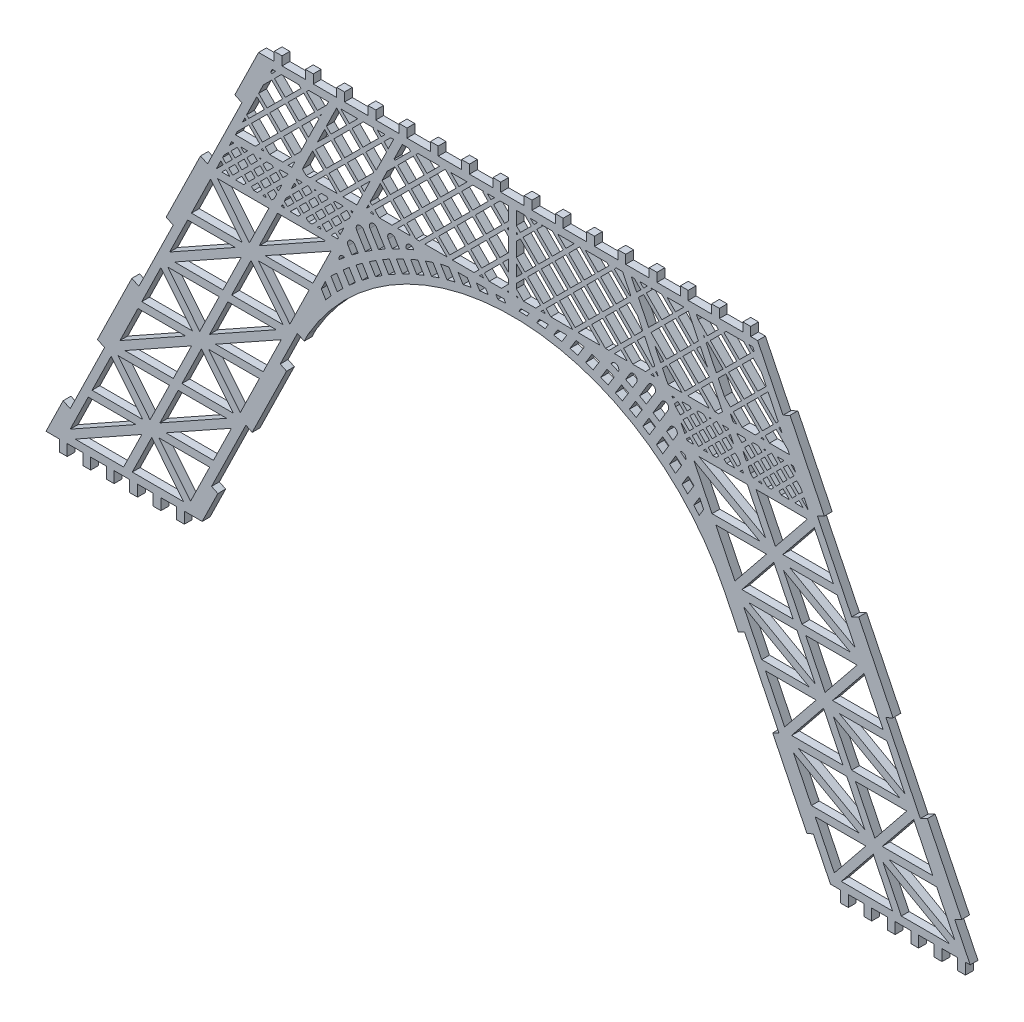
SolidWorks part; units mm, degrees
ref_plane "Front Plane" through (0, 0, 0) normal (0, 0, 1) x (1, 0, 0)
ref_plane "Top Plane" through (0, 0, 0) normal (0, 1, 0) x (1, 0, 0)
ref_plane "Right Plane" through (0, 0, 0) normal (1, 0, 0) x (0, 0, -1)
sketch "Sketch1" plane through (0, 0, 0) normal (0, 0, 1) x (1, 0, 0)
  line L352 (172.8252, 257.1681) -> (171.8349, 258.7906)
  line L353 (171.8349, 258.7906) -> (168.357, 258.7906)
  line L354 (168.357, 258.7906) -> (169.5804, 256.7861)
  line L355 (161.2702, 258.7906) -> (164.7849, 258.7906)
  line L356 (164.7849, 258.7906) -> (166.3142, 256.2849)
  line L357 (163.1634, 255.6888) -> (161.2702, 258.7906)
  line L358 (144.2581, 257.7696) -> (144.0734, 258.0721)
  line L359 (134.4627, 256.5092) -> (135.9979, 253.9938)
  line L360 (138.6985, 255.3276) -> (137.0234, 258.0721)
  line L361 (127.4127, 256.5092) -> (130.7215, 251.0879)
  line L362 (133.3286, 252.5749) -> (129.9734, 258.0721)
  line L363 (122.3453, 253.2948) -> (125.6465, 247.8861)
  line L364 (128.1608, 249.525) -> (124.906, 254.8577)
  line L365 (119.0483, 246.5583) -> (120.499, 244.1816)
  line L366 (122.9151, 245.9815) -> (121.6091, 248.1213)
  line L367 (112.4223, 241.4217) -> (105.5063, 227.2906)
  line L368 (105.5063, 227.2906) -> (87.1986, 227.2906)
  line L369 (87.1986, 227.2906) -> (112.4223, 241.4217)
  line L370 (112.4545, 233.0854) -> (114.8648, 229.1363)
  line L371 (117.0484, 231.317) -> (115.0152, 234.6483)
  line L372 (119.4562, 239.5103) -> (121.8265, 235.6268)
  line L373 (119.5305, 233.63) -> (117.1478, 237.534)
  line L374 (124.4828, 243.4128) -> (126.8351, 239.5589)
  line L375 (124.4307, 237.7399) -> (122.0712, 241.6056)
  line L376 (129.7239, 246.964) -> (132.0686, 243.1225)
  line L377 (129.5579, 241.4775) -> (127.211, 245.3228)
  line L378 (134.8931, 250.0116) -> (137.2401, 246.1663)
  line L379 (134.6293, 244.6854) -> (132.2846, 248.5269)
  line L380 (140.2702, 252.7525) -> (142.6288, 248.8881)
  line L381 (139.9169, 247.5729) -> (137.5653, 251.4258)
  line L382 (145.8429, 255.1729) -> (148.223, 251.2734)
  line L383 (145.4081, 250.1269) -> (143.04, 254.0068)
  line L384 (151.6165, 257.2642) -> (154.0285, 253.3123)
  line L385 (151.1074, 252.34) -> (148.7127, 256.2634)
  line L386 (104.038, 224.2906) -> (96.6905, 209.2778)
  line L387 (96.6905, 209.2778) -> (84.5881, 224.2906)
  line L388 (84.5881, 224.2906) -> (104.038, 224.2906)
  line L389 (66.2139, 242.3034) -> (78.3163, 227.2906)
  line L390 (78.3163, 227.2906) -> (58.8664, 227.2906)
  line L391 (58.8664, 227.2906) -> (66.2139, 242.3034)
  line L392 (81.7635, 223.0144) -> (94.036, 207.7906)
  line L393 (94.036, 207.7906) -> (74.3127, 207.7906)
  line L394 (74.3127, 207.7906) -> (81.7635, 223.0144)
  line L395 (47.1267, 203.3034) -> (59.2291, 188.2906)
  line L396 (59.2291, 188.2906) -> (39.7791, 188.2906)
  line L397 (39.7791, 188.2906) -> (47.1267, 203.3034)
  line L398 (62.0537, 189.5668) -> (49.7812, 204.7906)
  line L399 (49.7812, 204.7906) -> (69.5044, 204.7906)
  line L400 (69.5044, 204.7906) -> (62.0537, 189.5668)
  line L401 (77.6033, 170.2778) -> (65.5009, 185.2906)
  line L402 (65.5009, 185.2906) -> (84.9508, 185.2906)
  line L403 (84.9508, 185.2906) -> (77.6033, 170.2778)
  line L404 (62.6763, 184.0144) -> (74.9487, 168.7906)
  line L405 (74.9487, 168.7906) -> (55.2255, 168.7906)
  line L406 (55.2255, 168.7906) -> (62.6763, 184.0144)
  line L407 (28.0394, 164.3034) -> (40.1418, 149.2906)
  line L408 (40.1418, 149.2906) -> (20.6919, 149.2906)
  line L409 (20.6919, 149.2906) -> (28.0394, 164.3034)
  line L410 (58.516, 131.2778) -> (46.4136, 146.2906)
  line L411 (46.4136, 146.2906) -> (65.8636, 146.2906)
  line L412 (65.8636, 146.2906) -> (58.516, 131.2778)
  line L413 (42.9664, 150.5668) -> (30.694, 165.7906)
  line L414 (30.694, 165.7906) -> (50.4172, 165.7906)
  line L415 (50.4172, 165.7906) -> (42.9664, 150.5668)
  line L416 (36.1383, 129.7906) -> (55.8615, 129.7906)
  line L417 (55.8615, 129.7906) -> (43.589, 145.0144)
  line L418 (43.589, 145.0144) -> (36.1383, 129.7906)
  line L419 (50.4821, 210.1595) -> (57.3981, 224.2906)
  line L420 (57.3981, 224.2906) -> (75.7057, 224.2906)
  line L421 (75.7057, 224.2906) -> (50.4821, 210.1595)
  line L422 (77.9919, 222.1327) -> (70.9727, 207.7906)
  line L423 (70.9727, 207.7906) -> (52.3917, 207.7906)
  line L424 (52.3917, 207.7906) -> (77.9919, 222.1327)
  line L425 (93.335, 202.4217) -> (86.419, 188.2906)
  line L426 (86.419, 188.2906) -> (68.1114, 188.2906)
  line L427 (68.1114, 188.2906) -> (93.335, 202.4217)
  line L428 (65.8252, 190.4485) -> (72.8445, 204.7906)
  line L429 (72.8445, 204.7906) -> (91.4254, 204.7906)
  line L430 (91.4254, 204.7906) -> (65.8252, 190.4485)
  line L431 (31.3949, 171.1595) -> (38.3109, 185.2906)
  line L432 (38.3109, 185.2906) -> (56.6185, 185.2906)
  line L433 (56.6185, 185.2906) -> (31.3949, 171.1595)
  line L434 (58.9047, 183.1327) -> (51.8855, 168.7906)
  line L435 (51.8855, 168.7906) -> (33.3045, 168.7906)
  line L436 (33.3045, 168.7906) -> (58.9047, 183.1327)
  line L437 (74.2478, 163.4217) -> (67.3318, 149.2906)
  line L438 (67.3318, 149.2906) -> (49.0242, 149.2906)
  line L439 (49.0242, 149.2906) -> (74.2478, 163.4217)
  line L440 (46.738, 151.4485) -> (53.7572, 165.7906)
  line L441 (53.7572, 165.7906) -> (72.3382, 165.7906)
  line L442 (72.3382, 165.7906) -> (46.738, 151.4485)
  line L443 (14.2173, 129.7906) -> (39.8175, 144.1327)
  line L444 (39.8175, 144.1327) -> (32.7982, 129.7906)
  line L445 (32.7982, 129.7906) -> (14.2173, 129.7906)
  line L446 (19.2237, 146.2906) -> (12.3077, 132.1595)
  line L447 (12.3077, 132.1595) -> (37.5313, 146.2906)
  line L448 (37.5313, 146.2906) -> (19.2237, 146.2906)
  line L449 (175.745, 258.7906) -> (178.8849, 258.7906)
  line L450 (178.8849, 258.7906) -> (179.612, 257.5993)
  line L451 (176.5534, 257.4662) -> (175.745, 258.7906)
  line L452 (154.5897, 258.1852) -> (157.7349, 258.7906)
  line L453 (157.7349, 258.7906) -> (160.0546, 254.9899)
  line L454 (157.0221, 254.1999) -> (154.5897, 258.1852)
  line L455 (112.51, 226.6146) -> (110.2931, 230.2468)
  line L456 (110.2931, 230.2468) -> (108.729, 227.051)
  line L457 (108.729, 227.051) -> (110.4444, 224.2404)
  line L458 (110.4444, 224.2404) -> (112.51, 226.6146)
  line L459 (74.283, 258.7906) -> (73.4423, 257.073)
  line L460 (73.4423, 257.073) -> (75.16, 258.7906)
  line L461 (75.16, 258.7906) -> (74.283, 258.7906)
  line L462 (120.6093, 258.1498) -> (120.9229, 258.7906)
  line L463 (120.9229, 258.7906) -> (119.9685, 258.7906)
  line L464 (119.9685, 258.7906) -> (120.6093, 258.1498)
  line L465 (115.0525, 256.6832) -> (113.4882, 258.2475)
  line L466 (113.4882, 258.2475) -> (114.0313, 258.7906)
  line L467 (114.0313, 258.7906) -> (117.16, 258.7906)
  line L468 (117.16, 258.7906) -> (115.0525, 256.6832)
  line L469 (119.4974, 255.8781) -> (119.9122, 256.7256)
  line L470 (119.9122, 256.7256) -> (118.5642, 258.0735)
  line L471 (118.5642, 258.0735) -> (116.1132, 255.6225)
  line L472 (116.1132, 255.6225) -> (117.6775, 254.0582)
  line L473 (117.6775, 254.0582) -> (119.4974, 255.8781)
  line L474 (115.2965, 247.2945) -> (115.0499, 246.7906)
  line L475 (115.0499, 246.7906) -> (112.5313, 246.7906)
  line L476 (112.5313, 246.7906) -> (114.1658, 248.4251)
  line L477 (114.1658, 248.4251) -> (115.2965, 247.2945)
  line L478 (106.2908, 258.4215) -> (105.9217, 258.7906)
  line L479 (105.9217, 258.7906) -> (106.66, 258.7906)
  line L480 (106.66, 258.7906) -> (106.2908, 258.4215)
  line L481 (108.9158, 255.7965) -> (107.3515, 257.3608)
  line L482 (107.3515, 257.3608) -> (108.7813, 258.7906)
  line L483 (108.7813, 258.7906) -> (110.8237, 258.7906)
  line L484 (110.8237, 258.7906) -> (111.3669, 258.2475)
  line L485 (111.3669, 258.2475) -> (108.9158, 255.7965)
  line L486 (111.5408, 253.1715) -> (109.9765, 254.7358)
  line L487 (109.9765, 254.7358) -> (112.4275, 257.1868)
  line L488 (112.4275, 257.1868) -> (113.9919, 255.6225)
  line L489 (113.9919, 255.6225) -> (111.5408, 253.1715)
  line L490 (114.1658, 250.5465) -> (112.6015, 252.1108)
  line L491 (112.6015, 252.1108) -> (115.0525, 254.5618)
  line L492 (115.0525, 254.5618) -> (116.6169, 252.9975)
  line L493 (116.6169, 252.9975) -> (114.1658, 250.5465)
  line L494 (115.9935, 248.7187) -> (115.2265, 249.4858)
  line L495 (115.2265, 249.4858) -> (117.4641, 251.7234)
  line L496 (117.4641, 251.7234) -> (115.9935, 248.7187)
  line L497 (108.0291, 247.5384) -> (108.777, 246.7906)
  line L498 (108.777, 246.7906) -> (107.2813, 246.7906)
  line L499 (107.2813, 246.7906) -> (108.0291, 247.5384)
  line L500 (98.4528, 257.1148) -> (99.0935, 256.4741)
  line L501 (99.0935, 256.4741) -> (97.2245, 254.6051)
  line L502 (97.2245, 254.6051) -> (98.4528, 257.1148)
  line L503 (100.1541, 257.5348) -> (99.1498, 258.5391)
  line L504 (99.1498, 258.5391) -> (99.2729, 258.7906)
  line L505 (99.2729, 258.7906) -> (101.41, 258.7906)
  line L506 (101.41, 258.7906) -> (100.1541, 257.5348)
  line L507 (102.7791, 254.9098) -> (101.2148, 256.4741)
  line L508 (101.2148, 256.4741) -> (103.5313, 258.7906)
  line L509 (103.5313, 258.7906) -> (103.8003, 258.7906)
  line L510 (103.8003, 258.7906) -> (105.2302, 257.3608)
  line L511 (105.2302, 257.3608) -> (102.7791, 254.9098)
  line L512 (105.4041, 252.2848) -> (103.8398, 253.8491)
  line L513 (103.8398, 253.8491) -> (106.2908, 256.3001)
  line L514 (106.2908, 256.3001) -> (107.8552, 254.7358)
  line L515 (107.8552, 254.7358) -> (105.4041, 252.2848)
  line L516 (108.0291, 249.6598) -> (106.4648, 251.2241)
  line L517 (106.4648, 251.2241) -> (108.9158, 253.6751)
  line L518 (108.9158, 253.6751) -> (110.4802, 252.1108)
  line L519 (110.4802, 252.1108) -> (108.0291, 249.6598)
  line L520 (110.6541, 247.0348) -> (109.0898, 248.5991)
  line L521 (109.0898, 248.5991) -> (111.5408, 251.0501)
  line L522 (111.5408, 251.0501) -> (113.1052, 249.4858)
  line L523 (113.1052, 249.4858) -> (110.6541, 247.0348)
  line L524 (94.0174, 256.6481) -> (92.4531, 258.2124)
  line L525 (92.4531, 258.2124) -> (93.0313, 258.7906)
  line L526 (93.0313, 258.7906) -> (95.9329, 258.7906)
  line L527 (95.9329, 258.7906) -> (95.7153, 258.3459)
  line L528 (95.7153, 258.3459) -> (94.0174, 256.6481)
  line L529 (99.2674, 251.3981) -> (97.7031, 252.9624)
  line L530 (97.7031, 252.9624) -> (100.1541, 255.4134)
  line L531 (100.1541, 255.4134) -> (101.7185, 253.8491)
  line L532 (101.7185, 253.8491) -> (99.2674, 251.3981)
  line L533 (101.8924, 248.7731) -> (100.3281, 250.3374)
  line L534 (100.3281, 250.3374) -> (102.7791, 252.7884)
  line L535 (102.7791, 252.7884) -> (104.3435, 251.2241)
  line L536 (104.3435, 251.2241) -> (101.8924, 248.7731)
  line L537 (103.8749, 246.7906) -> (102.9531, 247.7124)
  line L538 (102.9531, 247.7124) -> (105.4041, 250.1634)
  line L539 (105.4041, 250.1634) -> (106.9685, 248.5991)
  line L540 (106.9685, 248.5991) -> (105.16, 246.7906)
  line L541 (105.16, 246.7906) -> (103.8749, 246.7906)
  line L542 (93.837, 247.6837) -> (94.6951, 246.8257)
  line L543 (94.6951, 246.8257) -> (94.66, 246.7906)
  line L544 (94.66, 246.7906) -> (93.3999, 246.7906)
  line L545 (93.3999, 246.7906) -> (93.837, 247.6837)
  line L546 (85.2557, 258.3864) -> (84.8515, 258.7906)
  line L547 (84.8515, 258.7906) -> (85.66, 258.7906)
  line L548 (85.66, 258.7906) -> (85.2557, 258.3864)
  line L549 (87.8807, 255.7614) -> (86.3164, 257.3257)
  line L550 (86.3164, 257.3257) -> (87.7813, 258.7906)
  line L551 (87.7813, 258.7906) -> (89.7536, 258.7906)
  line L552 (89.7536, 258.7906) -> (90.3318, 258.2124)
  line L553 (90.3318, 258.2124) -> (87.8807, 255.7614)
  line L554 (90.5057, 253.1364) -> (88.9414, 254.7007)
  line L555 (88.9414, 254.7007) -> (91.3924, 257.1517)
  line L556 (91.3924, 257.1517) -> (92.9568, 255.5874)
  line L557 (92.9568, 255.5874) -> (90.5057, 253.1364)
  line L558 (92.2916, 251.3505) -> (91.5664, 252.0757)
  line L559 (91.5664, 252.0757) -> (93.6819, 254.1912)
  line L560 (93.6819, 254.1912) -> (92.2916, 251.3505)
  line L561 (95.7557, 247.8864) -> (94.5341, 249.108)
  line L562 (94.5341, 249.108) -> (95.1911, 250.4504)
  line L563 (95.1911, 250.4504) -> (96.6424, 251.9017)
  line L564 (96.6424, 251.9017) -> (98.2068, 250.3374)
  line L565 (98.2068, 250.3374) -> (95.7557, 247.8864)
  line L566 (96.8515, 246.7906) -> (96.8164, 246.8257)
  line L567 (96.8164, 246.8257) -> (99.2674, 249.2767)
  line L568 (99.2674, 249.2767) -> (100.8318, 247.7124)
  line L569 (100.8318, 247.7124) -> (99.91, 246.7906)
  line L570 (99.91, 246.7906) -> (96.8515, 246.7906)
  line L571 (110.5126, 243.7906) -> (84.9124, 229.4485)
  line L572 (84.9124, 229.4485) -> (91.9317, 243.7906)
  line L573 (91.9317, 243.7906) -> (110.5126, 243.7906)
  line L574 (86.994, 247.5033) -> (87.7068, 246.7906)
  line L575 (87.7068, 246.7906) -> (86.2813, 246.7906)
  line L576 (86.2813, 246.7906) -> (86.994, 247.5033)
  line L577 (79.119, 257.4997) -> (77.8281, 258.7906)
  line L578 (77.8281, 258.7906) -> (80.41, 258.7906)
  line L579 (80.41, 258.7906) -> (79.119, 257.4997)
  line L580 (81.744, 254.8747) -> (80.1797, 256.439)
  line L581 (80.1797, 256.439) -> (82.5313, 258.7906)
  line L582 (82.5313, 258.7906) -> (82.7302, 258.7906)
  line L583 (82.7302, 258.7906) -> (84.1951, 257.3257)
  line L584 (84.1951, 257.3257) -> (81.744, 254.8747)
  line L585 (84.369, 252.2497) -> (82.8047, 253.814)
  line L586 (82.8047, 253.814) -> (85.2557, 256.265)
  line L587 (85.2557, 256.265) -> (86.8201, 254.7007)
  line L588 (86.8201, 254.7007) -> (84.369, 252.2497)
  line L589 (86.994, 249.6247) -> (85.4297, 251.189)
  line L590 (85.4297, 251.189) -> (87.8807, 253.64)
  line L591 (87.8807, 253.64) -> (89.4451, 252.0757)
  line L592 (89.4451, 252.0757) -> (86.994, 249.6247)
  line L593 (89.619, 246.9997) -> (88.0547, 248.564)
  line L594 (88.0547, 248.564) -> (90.5057, 251.015)
  line L595 (90.5057, 251.015) -> (91.5945, 249.9262)
  line L596 (91.5945, 249.9262) -> (90.6829, 248.0636)
  line L597 (90.6829, 248.0636) -> (89.619, 246.9997)
  line L598 (75.6073, 253.988) -> (74.043, 255.5523)
  line L599 (74.043, 255.5523) -> (76.494, 258.0033)
  line L600 (76.494, 258.0033) -> (78.0584, 256.439)
  line L601 (78.0584, 256.439) -> (75.6073, 253.988)
  line L602 (78.2323, 251.363) -> (76.668, 252.9273)
  line L603 (76.668, 252.9273) -> (79.119, 255.3783)
  line L604 (79.119, 255.3783) -> (80.6834, 253.814)
  line L605 (80.6834, 253.814) -> (78.2323, 251.363)
  line L606 (80.8573, 248.738) -> (79.293, 250.3023)
  line L607 (79.293, 250.3023) -> (81.744, 252.7533)
  line L608 (81.744, 252.7533) -> (83.3084, 251.189)
  line L609 (83.3084, 251.189) -> (80.8573, 248.738)
  line L610 (82.8047, 246.7906) -> (81.918, 247.6773)
  line L611 (81.918, 247.6773) -> (84.369, 250.1283)
  line L612 (84.369, 250.1283) -> (85.9334, 248.564)
  line L613 (85.9334, 248.564) -> (84.16, 246.7906)
  line L614 (84.16, 246.7906) -> (82.8047, 246.7906)
  line L615 (88.5917, 243.7906) -> (81.1409, 228.5668)
  line L616 (81.1409, 228.5668) -> (68.8684, 243.7906)
  line L617 (68.8684, 243.7906) -> (88.5917, 243.7906)
  line L618 (72.0956, 248.355) -> (73.66, 246.7906)
  line L619 (73.66, 246.7906) -> (70.5313, 246.7906)
  line L620 (70.5313, 246.7906) -> (72.0956, 248.355)
  line L621 (70.1351, 250.3155) -> (71.035, 249.4156)
  line L622 (71.035, 249.4156) -> (68.41, 246.7906)
  line L623 (68.41, 246.7906) -> (70.1351, 250.3155)
  line L624 (72.0956, 250.4763) -> (70.8322, 251.7397)
  line L625 (70.8322, 251.7397) -> (71.4089, 252.9183)
  line L626 (71.4089, 252.9183) -> (72.9823, 254.4917)
  line L627 (72.9823, 254.4917) -> (74.5467, 252.9273)
  line L628 (74.5467, 252.9273) -> (72.0956, 250.4763)
  line L629 (74.7206, 247.8513) -> (73.1563, 249.4156)
  line L630 (73.1563, 249.4156) -> (75.6073, 251.8667)
  line L631 (75.6073, 251.8667) -> (77.1717, 250.3023)
  line L632 (77.1717, 250.3023) -> (74.7206, 247.8513)
  line L633 (75.7813, 246.7906) -> (78.2323, 249.2417)
  line L634 (78.2323, 249.2417) -> (79.7967, 247.6773)
  line L635 (79.7967, 247.6773) -> (78.91, 246.7906)
  line L636 (78.91, 246.7906) -> (75.7813, 246.7906)
  line L637 (140.5096, 264.2689) -> (142.9878, 261.7906)
  line L638 (142.9878, 261.7906) -> (138.0313, 261.7906)
  line L639 (138.0313, 261.7906) -> (140.5096, 264.2689)
  line L640 (156.9723, 261.8529) -> (156.91, 261.7906)
  line L641 (156.91, 261.7906) -> (148.5313, 261.7906)
  line L642 (148.5313, 261.7906) -> (152.783, 266.0423)
  line L643 (152.783, 266.0423) -> (156.9723, 261.8529)
  line L644 (134.4719, 286.4747) -> (136.5075, 290.6338)
  line L645 (136.5075, 290.6338) -> (135.3745, 290.6338)
  line L646 (135.3745, 290.6338) -> (132.8436, 288.1029)
  line L647 (132.8436, 288.1029) -> (134.4719, 286.4747)
  line L648 (130.3127, 290.6338) -> (133.2532, 290.6338)
  line L649 (133.2532, 290.6338) -> (131.783, 289.1636)
  line L650 (131.783, 289.1636) -> (130.3127, 290.6338)
  line L651 (128.2362, 262.4955) -> (128.9411, 261.7906)
  line L652 (128.9411, 261.7906) -> (127.5313, 261.7906)
  line L653 (127.5313, 261.7906) -> (128.2362, 262.4955)
  line L654 (141.5702, 265.3296) -> (147.533, 271.2923)
  line L655 (147.533, 271.2923) -> (151.7223, 267.1029)
  line L656 (151.7223, 267.1029) -> (146.41, 261.7906)
  line L657 (146.41, 261.7906) -> (145.1092, 261.7906)
  line L658 (145.1092, 261.7906) -> (141.5702, 265.3296)
  line L659 (136.3202, 270.5796) -> (142.283, 276.5423)
  line L660 (142.283, 276.5423) -> (146.4723, 272.3529)
  line L661 (146.4723, 272.3529) -> (140.5096, 266.3902)
  line L662 (140.5096, 266.3902) -> (136.3202, 270.5796)
  line L663 (132.0987, 274.8011) -> (134.0703, 278.8296)
  line L664 (134.0703, 278.8296) -> (137.033, 281.7923)
  line L665 (137.033, 281.7923) -> (141.2223, 277.6029)
  line L666 (141.2223, 277.6029) -> (135.2596, 271.6402)
  line L667 (135.2596, 271.6402) -> (132.0987, 274.8011)
  line L668 (124.5434, 266.1883) -> (122.3911, 261.7906)
  line L669 (122.3911, 261.7906) -> (117.0313, 261.7906)
  line L670 (117.0313, 261.7906) -> (122.9862, 267.7455)
  line L671 (122.9862, 267.7455) -> (124.5434, 266.1883)
  line L672 (127.1755, 263.5562) -> (126.039, 262.4196)
  line L673 (126.039, 262.4196) -> (126.7859, 263.9458)
  line L674 (126.7859, 263.9458) -> (127.1755, 263.5562)
  line L675 (129.2968, 263.5562) -> (135.2596, 269.5189)
  line L676 (135.2596, 269.5189) -> (139.4489, 265.3296)
  line L677 (139.4489, 265.3296) -> (135.91, 261.7906)
  line L678 (135.91, 261.7906) -> (131.0624, 261.7906)
  line L679 (131.0624, 261.7906) -> (129.2968, 263.5562)
  line L680 (127.483, 265.37) -> (131.4016, 273.3768)
  line L681 (131.4016, 273.3768) -> (134.1989, 270.5796)
  line L682 (134.1989, 270.5796) -> (128.2362, 264.6168)
  line L683 (128.2362, 264.6168) -> (127.483, 265.37)
  line L684 (125.2405, 267.6125) -> (127.5287, 272.2881)
  line L685 (127.5287, 272.2881) -> (124.0468, 268.8062)
  line L686 (124.0468, 268.8062) -> (125.2405, 267.6125)
  line L687 (175.2532, 290.6338) -> (172.5002, 290.6338)
  line L688 (172.5002, 290.6338) -> (173.8767, 289.2574)
  line L689 (173.8767, 289.2574) -> (175.2532, 290.6338)
  line L690 (170.3299, 262.5892) -> (171.1286, 261.7906)
  line L691 (171.1286, 261.7906) -> (169.5313, 261.7906)
  line L692 (169.5313, 261.7906) -> (170.3299, 262.5892)
  line L693 (169.2693, 263.6499) -> (167.41, 261.7906)
  line L694 (167.41, 261.7906) -> (159.156, 261.7906)
  line L695 (159.156, 261.7906) -> (159.0936, 261.8529)
  line L696 (159.0936, 261.8529) -> (165.0799, 267.8392)
  line L697 (165.0799, 267.8392) -> (169.2693, 263.6499)
  line L698 (166.1406, 268.8999) -> (172.1033, 274.8626)
  line L699 (172.1033, 274.8626) -> (176.2927, 270.6733)
  line L700 (176.2927, 270.6733) -> (170.3299, 264.7106)
  line L701 (170.3299, 264.7106) -> (166.1406, 268.8999)
  line L702 (106.5313, 261.7906) -> (114.8471, 261.7906)
  line L703 (114.8471, 261.7906) -> (110.6892, 265.9485)
  line L704 (110.6892, 265.9485) -> (106.5313, 261.7906)
  line L705 (88.598, 288.0398) -> (88.6286, 288.0092)
  line L706 (88.6286, 288.0092) -> (88.5393, 287.92)
  line L707 (88.5393, 287.92) -> (88.598, 288.0398)
  line L708 (91.2532, 290.6338) -> (89.8676, 290.6338)
  line L709 (89.8676, 290.6338) -> (89.295, 289.464)
  line L710 (89.295, 289.464) -> (89.6892, 289.0699)
  line L711 (89.6892, 289.0699) -> (91.2532, 290.6338)
  line L712 (102.9217, 261.7906) -> (104.41, 261.7906)
  line L713 (104.41, 261.7906) -> (109.6286, 267.0092)
  line L714 (109.6286, 267.0092) -> (105.4392, 271.1985)
  line L715 (105.4392, 271.1985) -> (105.2558, 271.0151)
  line L716 (105.2558, 271.0151) -> (101.4577, 263.2546)
  line L717 (101.4577, 263.2546) -> (102.9217, 261.7906)
  line L718 (100.7412, 261.7906) -> (100.8003, 261.7906)
  line L719 (100.8003, 261.7906) -> (100.7606, 261.8303)
  line L720 (100.7606, 261.8303) -> (100.7412, 261.7906)
  line L721 (98.4158, 264.1751) -> (98.5181, 264.0728)
  line L722 (98.5181, 264.0728) -> (97.4012, 261.7906)
  line L723 (97.4012, 261.7906) -> (96.0313, 261.7906)
  line L724 (96.0313, 261.7906) -> (98.4158, 264.1751)
  line L725 (87.9158, 276.7965) -> (84.6793, 280.033)
  line L726 (84.6793, 280.033) -> (86.506, 283.7653)
  line L727 (86.506, 283.7653) -> (89.6892, 286.9485)
  line L728 (89.6892, 286.9485) -> (93.8786, 282.7592)
  line L729 (93.8786, 282.7592) -> (87.9158, 276.7965)
  line L730 (93.1658, 271.5465) -> (88.9765, 275.7358)
  line L731 (88.9765, 275.7358) -> (94.9392, 281.6985)
  line L732 (94.9392, 281.6985) -> (99.1286, 277.5092)
  line L733 (99.1286, 277.5092) -> (93.1658, 271.5465)
  line L734 (98.4158, 266.2965) -> (94.2265, 270.4858)
  line L735 (94.2265, 270.4858) -> (100.1892, 276.4485)
  line L736 (100.1892, 276.4485) -> (103.1338, 273.5039)
  line L737 (103.1338, 273.5039) -> (100.7476, 268.6282)
  line L738 (100.7476, 268.6282) -> (98.4158, 266.2965)
  line L739 (100.0978, 290.6338) -> (100.9255, 289.8062)
  line L740 (100.9255, 289.8062) -> (94.9392, 283.8199)
  line L741 (94.9392, 283.8199) -> (90.7499, 288.0092)
  line L742 (90.7499, 288.0092) -> (93.3745, 290.6338)
  line L743 (93.3745, 290.6338) -> (100.0978, 290.6338)
  line L744 (117.7362, 272.9955) -> (121.9255, 268.8062)
  line L745 (121.9255, 268.8062) -> (115.9392, 262.8199)
  line L746 (115.9392, 262.8199) -> (111.7499, 267.0092)
  line L747 (111.7499, 267.0092) -> (117.7362, 272.9955)
  line L748 (112.4862, 278.2455) -> (116.6755, 274.0562)
  line L749 (116.6755, 274.0562) -> (110.6892, 268.0699)
  line L750 (110.6892, 268.0699) -> (106.4999, 272.2592)
  line L751 (106.4999, 272.2592) -> (112.4862, 278.2455)
  line L752 (110.0075, 280.7241) -> (111.4255, 279.3062)
  line L753 (111.4255, 279.3062) -> (107.2892, 275.1698)
  line L754 (107.2892, 275.1698) -> (110.0075, 280.7241)
  line L755 (107.2362, 283.4955) -> (107.765, 282.9666)
  line L756 (107.765, 282.9666) -> (103.8309, 274.9282)
  line L757 (103.8309, 274.9282) -> (101.2499, 277.5092)
  line L758 (101.2499, 277.5092) -> (107.2362, 283.4955)
  line L759 (101.9862, 288.7455) -> (106.1755, 284.5562)
  line L760 (106.1755, 284.5562) -> (100.1892, 278.5699)
  line L761 (100.1892, 278.5699) -> (95.9999, 282.7592)
  line L762 (95.9999, 282.7592) -> (101.9862, 288.7455)
  line L763 (107.2362, 285.6168) -> (103.0468, 289.8062)
  line L764 (103.0468, 289.8062) -> (103.8745, 290.6338)
  line L765 (103.8745, 290.6338) -> (111.5175, 290.6338)
  line L766 (111.5175, 290.6338) -> (110.8123, 289.1929)
  line L767 (110.8123, 289.1929) -> (107.2362, 285.6168)
  line L768 (108.4621, 284.3909) -> (108.2968, 284.5562)
  line L769 (108.2968, 284.5562) -> (108.7789, 285.0382)
  line L770 (108.7789, 285.0382) -> (108.4621, 284.3909)
  line L771 (124.7596, 280.0189) -> (128.9489, 275.8296)
  line L772 (128.9489, 275.8296) -> (122.9862, 269.8668)
  line L773 (122.9862, 269.8668) -> (118.7968, 274.0562)
  line L774 (118.7968, 274.0562) -> (124.7596, 280.0189)
  line L775 (129.8562, 277.0436) -> (133.7748, 285.0504)
  line L776 (133.7748, 285.0504) -> (131.783, 287.0423)
  line L777 (131.783, 287.0423) -> (125.8202, 281.0796)
  line L778 (125.8202, 281.0796) -> (129.8562, 277.0436)
  line L779 (124.7596, 282.1402) -> (120.5702, 286.3296)
  line L780 (120.5702, 286.3296) -> (124.8745, 290.6338)
  line L781 (124.8745, 290.6338) -> (128.8945, 290.6338)
  line L782 (128.8945, 290.6338) -> (128.543, 290.2823)
  line L783 (128.543, 290.2823) -> (130.7223, 288.1029)
  line L784 (130.7223, 288.1029) -> (124.7596, 282.1402)
  line L785 (122.7532, 290.6338) -> (116.2659, 290.6338)
  line L786 (116.2659, 290.6338) -> (119.5096, 287.3902)
  line L787 (119.5096, 287.3902) -> (122.7532, 290.6338)
  line L788 (114.6233, 290.1552) -> (118.4489, 286.3296)
  line L789 (118.4489, 286.3296) -> (112.4862, 280.3668)
  line L790 (112.4862, 280.3668) -> (110.7046, 282.1484)
  line L791 (110.7046, 282.1484) -> (114.6233, 290.1552)
  line L792 (119.5096, 285.2689) -> (123.6989, 281.0796)
  line L793 (123.6989, 281.0796) -> (117.7362, 275.1168)
  line L794 (117.7362, 275.1168) -> (113.5468, 279.3062)
  line L795 (113.5468, 279.3062) -> (119.5096, 285.2689)
  line L796 (142.2853, 290.6338) -> (143.0193, 289.8999)
  line L797 (143.0193, 289.8999) -> (137.033, 283.9136)
  line L798 (137.033, 283.9136) -> (136.7144, 284.2322)
  line L799 (136.7144, 284.2322) -> (139.8475, 290.6338)
  line L800 (139.8475, 290.6338) -> (142.2853, 290.6338)
  line L801 (159.8299, 273.0892) -> (164.0193, 268.8999)
  line L802 (164.0193, 268.8999) -> (158.033, 262.9136)
  line L803 (158.033, 262.9136) -> (153.8436, 267.1029)
  line L804 (153.8436, 267.1029) -> (159.8299, 273.0892)
  line L805 (154.5799, 278.3392) -> (158.7693, 274.1499)
  line L806 (158.7693, 274.1499) -> (152.783, 268.1636)
  line L807 (152.783, 268.1636) -> (148.5936, 272.3529)
  line L808 (148.5936, 272.3529) -> (154.5799, 278.3392)
  line L809 (149.3299, 283.5892) -> (153.5193, 279.3999)
  line L810 (153.5193, 279.3999) -> (147.533, 273.4136)
  line L811 (147.533, 273.4136) -> (143.3436, 277.6029)
  line L812 (143.3436, 277.6029) -> (149.3299, 283.5892)
  line L813 (144.0799, 288.8392) -> (148.2693, 284.6499)
  line L814 (148.2693, 284.6499) -> (142.283, 278.6636)
  line L815 (142.283, 278.6636) -> (138.0936, 282.8529)
  line L816 (138.0936, 282.8529) -> (144.0799, 288.8392)
  line L817 (154.2532, 290.6338) -> (145.8745, 290.6338)
  line L818 (145.8745, 290.6338) -> (145.1406, 289.8999)
  line L819 (145.1406, 289.8999) -> (149.3299, 285.7106)
  line L820 (149.3299, 285.7106) -> (154.2532, 290.6338)
  line L821 (166.8533, 280.1126) -> (171.0427, 275.9233)
  line L822 (171.0427, 275.9233) -> (165.0799, 269.9606)
  line L823 (165.0799, 269.9606) -> (160.8906, 274.1499)
  line L824 (160.8906, 274.1499) -> (166.8533, 280.1126)
  line L825 (167.914, 281.1733) -> (173.8767, 287.136)
  line L826 (173.8767, 287.136) -> (178.0661, 282.9467)
  line L827 (178.0661, 282.9467) -> (172.1033, 276.984)
  line L828 (172.1033, 276.984) -> (167.914, 281.1733)
  line L829 (166.8533, 282.234) -> (162.664, 286.4233)
  line L830 (162.664, 286.4233) -> (166.8745, 290.6338)
  line L831 (166.8745, 290.6338) -> (171.082, 290.6338)
  line L832 (171.082, 290.6338) -> (170.7305, 290.2823)
  line L833 (170.7305, 290.2823) -> (172.8161, 288.1967)
  line L834 (172.8161, 288.1967) -> (166.8533, 282.234)
  line L835 (161.6033, 285.3626) -> (165.7927, 281.1733)
  line L836 (165.7927, 281.1733) -> (159.8299, 275.2106)
  line L837 (159.8299, 275.2106) -> (155.6406, 279.3999)
  line L838 (155.6406, 279.3999) -> (161.6033, 285.3626)
  line L839 (164.7532, 290.6338) -> (158.4534, 290.6338)
  line L840 (158.4534, 290.6338) -> (161.6033, 287.484)
  line L841 (161.6033, 287.484) -> (164.7532, 290.6338)
  line L842 (156.3533, 290.6126) -> (160.5427, 286.4233)
  line L843 (160.5427, 286.4233) -> (154.5799, 280.4606)
  line L844 (154.5799, 280.4606) -> (150.3906, 284.6499)
  line L845 (150.3906, 284.6499) -> (156.3533, 290.6126)
  line L846 (88.8749, 261.7906) -> (93.91, 261.7906)
  line L847 (93.91, 261.7906) -> (97.3552, 265.2358)
  line L848 (97.3552, 265.2358) -> (93.1658, 269.4251)
  line L849 (93.1658, 269.4251) -> (87.2031, 263.4624)
  line L850 (87.2031, 263.4624) -> (88.8749, 261.7906)
  line L851 (79.3665, 269.1776) -> (79.8318, 268.7124)
  line L852 (79.8318, 268.7124) -> (78.4747, 267.3553)
  line L853 (78.4747, 267.3553) -> (79.3665, 269.1776)
  line L854 (76.4413, 263.2006) -> (75.7512, 261.7906)
  line L855 (75.7512, 261.7906) -> (83.41, 261.7906)
  line L856 (83.41, 261.7906) -> (85.0818, 263.4624)
  line L857 (85.0818, 263.4624) -> (80.8924, 267.6517)
  line L858 (80.8924, 267.6517) -> (76.4413, 263.2006)
  line L859 (85.5313, 261.7906) -> (86.7536, 261.7906)
  line L860 (86.7536, 261.7906) -> (86.1424, 262.4017)
  line L861 (86.1424, 262.4017) -> (85.5313, 261.7906)
  line L862 (86.1424, 264.5231) -> (81.9531, 268.7124)
  line L863 (81.9531, 268.7124) -> (87.9158, 274.6751)
  line L864 (87.9158, 274.6751) -> (92.1052, 270.4858)
  line L865 (92.1052, 270.4858) -> (86.1424, 264.5231)
  line L866 (80.8924, 269.7731) -> (80.0636, 270.6019)
  line L867 (80.0636, 270.6019) -> (83.9823, 278.6087)
  line L868 (83.9823, 278.6087) -> (86.8552, 275.7358)
  line L869 (86.8552, 275.7358) -> (80.8924, 269.7731)
  line L870 (194.7311, 256.7861) -> (195.9545, 258.7906)
  line L871 (195.9545, 258.7906) -> (192.4767, 258.7906)
  line L872 (192.4767, 258.7906) -> (191.4864, 257.1681)
  line L873 (197.9973, 256.2849) -> (199.5267, 258.7906)
  line L874 (199.5267, 258.7906) -> (203.0413, 258.7906)
  line L875 (203.0413, 258.7906) -> (201.1481, 255.6888)
  line L876 (220.0535, 257.7696) -> (220.2381, 258.0721)
  line L877 (229.8488, 256.5092) -> (228.3136, 253.9938)
  line L878 (225.613, 255.3276) -> (227.2881, 258.0721)
  line L879 (236.8988, 256.5092) -> (233.59, 251.0879)
  line L880 (230.9829, 252.5749) -> (234.3381, 258.0721)
  line L881 (241.9662, 253.2948) -> (238.6651, 247.8861)
  line L882 (236.1507, 249.525) -> (239.4055, 254.8577)
  line L883 (245.2632, 246.5583) -> (243.8125, 244.1816)
  line L884 (241.3964, 245.9815) -> (242.7025, 248.1213)
  line L885 (277.1129, 227.2906) -> (258.8052, 227.2906)
  line L886 (258.8052, 227.2906) -> (251.8892, 241.4217)
  line L887 (251.8892, 241.4217) -> (277.1129, 227.2906)
  line L888 (249.2963, 234.6483) -> (247.2631, 231.317)
  line L889 (249.4468, 229.1363) -> (251.8571, 233.0854)
  line L890 (244.8553, 239.5103) -> (242.485, 235.6268)
  line L891 (244.781, 233.63) -> (247.1637, 237.534)
  line L892 (239.8287, 243.4128) -> (237.4765, 239.5589)
  line L893 (239.8808, 237.7399) -> (242.2403, 241.6056)
  line L894 (234.5876, 246.964) -> (232.2429, 243.1225)
  line L895 (234.7536, 241.4775) -> (237.1005, 245.3228)
  line L896 (229.4184, 250.0116) -> (227.0714, 246.1663)
  line L897 (229.6822, 244.6854) -> (232.0269, 248.5269)
  line L898 (224.0413, 252.7525) -> (221.6827, 248.8881)
  line L899 (224.3946, 247.5729) -> (226.7462, 251.4258)
  line L900 (218.4686, 255.1729) -> (216.0886, 251.2734)
  line L901 (218.9034, 250.1269) -> (221.2715, 254.0068)
  line L902 (212.695, 257.2642) -> (210.283, 253.3123)
  line L903 (213.2042, 252.34) -> (215.5988, 256.2634)
  line L904 (279.7234, 224.2906) -> (267.621, 209.2778)
  line L905 (267.621, 209.2778) -> (260.2735, 224.2906)
  line L906 (260.2735, 224.2906) -> (279.7234, 224.2906)
  line L907 (298.0976, 242.3034) -> (285.9952, 227.2906)
  line L908 (285.9952, 227.2906) -> (305.4452, 227.2906)
  line L909 (305.4452, 227.2906) -> (298.0976, 242.3034)
  line L910 (282.548, 223.0144) -> (270.2756, 207.7906)
  line L911 (270.2756, 207.7906) -> (289.9988, 207.7906)
  line L912 (289.9988, 207.7906) -> (282.548, 223.0144)
  line L913 (317.1849, 203.3034) -> (305.0825, 188.2906)
  line L914 (305.0825, 188.2906) -> (324.5324, 188.2906)
  line L915 (324.5324, 188.2906) -> (317.1849, 203.3034)
  line L916 (302.2578, 189.5668) -> (314.5303, 204.7906)
  line L917 (314.5303, 204.7906) -> (294.8071, 204.7906)
  line L918 (294.8071, 204.7906) -> (302.2578, 189.5668)
  line L919 (286.7082, 170.2778) -> (298.8106, 185.2906)
  line L920 (298.8106, 185.2906) -> (279.3607, 185.2906)
  line L921 (279.3607, 185.2906) -> (286.7082, 170.2778)
  line L922 (301.6353, 184.0144) -> (289.3628, 168.7906)
  line L923 (289.3628, 168.7906) -> (309.086, 168.7906)
  line L924 (309.086, 168.7906) -> (301.6353, 184.0144)
  line L925 (336.2721, 164.3034) -> (324.1697, 149.2906)
  line L926 (324.1697, 149.2906) -> (343.6196, 149.2906)
  line L927 (343.6196, 149.2906) -> (336.2721, 164.3034)
  line L928 (305.7955, 131.2778) -> (317.8979, 146.2906)
  line L929 (317.8979, 146.2906) -> (298.4479, 146.2906)
  line L930 (298.4479, 146.2906) -> (305.7955, 131.2778)
  line L931 (321.3451, 150.5668) -> (333.6175, 165.7906)
  line L932 (333.6175, 165.7906) -> (313.8943, 165.7906)
  line L933 (313.8943, 165.7906) -> (321.3451, 150.5668)
  line L934 (320.7225, 145.0144) -> (308.45, 129.7906)
  line L935 (308.45, 129.7906) -> (328.1733, 129.7906)
  line L936 (328.1733, 129.7906) -> (320.7225, 145.0144)
  line L937 (288.6058, 224.2906) -> (306.9134, 224.2906)
  line L938 (306.9134, 224.2906) -> (313.8294, 210.1595)
  line L939 (313.8294, 210.1595) -> (288.6058, 224.2906)
  line L940 (286.3196, 222.1327) -> (293.3388, 207.7906)
  line L941 (293.3388, 207.7906) -> (311.9198, 207.7906)
  line L942 (311.9198, 207.7906) -> (286.3196, 222.1327)
  line L943 (296.2001, 188.2906) -> (277.8925, 188.2906)
  line L944 (277.8925, 188.2906) -> (270.9765, 202.4217)
  line L945 (270.9765, 202.4217) -> (296.2001, 188.2906)
  line L946 (298.4863, 190.4485) -> (291.4671, 204.7906)
  line L947 (291.4671, 204.7906) -> (272.8861, 204.7906)
  line L948 (272.8861, 204.7906) -> (298.4863, 190.4485)
  line L949 (307.693, 185.2906) -> (326.0006, 185.2906)
  line L950 (326.0006, 185.2906) -> (332.9166, 171.1595)
  line L951 (332.9166, 171.1595) -> (307.693, 185.2906)
  line L952 (305.4068, 183.1327) -> (312.4261, 168.7906)
  line L953 (312.4261, 168.7906) -> (331.007, 168.7906)
  line L954 (331.007, 168.7906) -> (305.4068, 183.1327)
  line L955 (315.2873, 149.2906) -> (296.9797, 149.2906)
  line L956 (296.9797, 149.2906) -> (290.0637, 163.4217)
  line L957 (290.0637, 163.4217) -> (315.2873, 149.2906)
  line L958 (317.5735, 151.4485) -> (310.5543, 165.7906)
  line L959 (310.5543, 165.7906) -> (291.9733, 165.7906)
  line L960 (291.9733, 165.7906) -> (317.5735, 151.4485)
  line L961 (350.0942, 129.7906) -> (324.494, 144.1327)
  line L962 (324.494, 144.1327) -> (331.5133, 129.7906)
  line L963 (331.5133, 129.7906) -> (350.0942, 129.7906)
  line L964 (326.7802, 146.2906) -> (352.0039, 132.1595)
  line L965 (352.0039, 132.1595) -> (345.0879, 146.2906)
  line L966 (345.0879, 146.2906) -> (326.7802, 146.2906)
  line L967 (184.6995, 257.5993) -> (185.4267, 258.7906)
  line L968 (185.4267, 258.7906) -> (188.5665, 258.7906)
  line L969 (188.5665, 258.7906) -> (187.7581, 257.4662)
  line L970 (204.2569, 254.9899) -> (206.5767, 258.7906)
  line L971 (206.5767, 258.7906) -> (209.7218, 258.1852)
  line L972 (209.7218, 258.1852) -> (207.2894, 254.1999)
  line L973 (251.8015, 226.6146) -> (254.0184, 230.2468)
  line L974 (254.0184, 230.2468) -> (255.5825, 227.051)
  line L975 (255.5825, 227.051) -> (253.8671, 224.2404)
  line L976 (253.8671, 224.2404) -> (251.8015, 226.6146)
  line L977 (289.1515, 258.7906) -> (290.8692, 257.073)
  line L978 (290.8692, 257.073) -> (290.0286, 258.7906)
  line L979 (290.0286, 258.7906) -> (289.1515, 258.7906)
  line L980 (244.3431, 258.7906) -> (243.3886, 258.7906)
  line L981 (243.3886, 258.7906) -> (243.7023, 258.1498)
  line L982 (243.7023, 258.1498) -> (244.3431, 258.7906)
  line L983 (249.259, 256.6832) -> (250.8233, 258.2475)
  line L984 (250.8233, 258.2475) -> (250.2802, 258.7906)
  line L985 (250.2802, 258.7906) -> (247.1515, 258.7906)
  line L986 (247.1515, 258.7906) -> (249.259, 256.6832)
  line L987 (246.634, 254.0582) -> (248.1983, 255.6225)
  line L988 (248.1983, 255.6225) -> (245.7473, 258.0735)
  line L989 (245.7473, 258.0735) -> (244.3993, 256.7256)
  line L990 (244.3993, 256.7256) -> (244.8141, 255.8781)
  line L991 (244.8141, 255.8781) -> (246.634, 254.0582)
  line L992 (250.1457, 248.4251) -> (251.7802, 246.7906)
  line L993 (251.7802, 246.7906) -> (249.2616, 246.7906)
  line L994 (249.2616, 246.7906) -> (249.015, 247.2945)
  line L995 (249.015, 247.2945) -> (250.1457, 248.4251)
  line L996 (258.0207, 258.4215) -> (258.3898, 258.7906)
  line L997 (258.3898, 258.7906) -> (257.6515, 258.7906)
  line L998 (257.6515, 258.7906) -> (258.0207, 258.4215)
  line L999 (255.3957, 255.7965) -> (256.96, 257.3608)
  line L1000 (256.96, 257.3608) -> (255.5302, 258.7906)
  line L1001 (255.5302, 258.7906) -> (253.4878, 258.7906)
  line L1002 (253.4878, 258.7906) -> (252.9447, 258.2475)
  line L1003 (252.9447, 258.2475) -> (255.3957, 255.7965)
  line L1004 (252.7707, 253.1715) -> (254.335, 254.7358)
  line L1005 (254.335, 254.7358) -> (251.884, 257.1868)
  line L1006 (251.884, 257.1868) -> (250.3197, 255.6225)
  line L1007 (250.3197, 255.6225) -> (252.7707, 253.1715)
  line L1008 (250.1457, 250.5465) -> (251.71, 252.1108)
  line L1009 (251.71, 252.1108) -> (249.259, 254.5618)
  line L1010 (249.259, 254.5618) -> (247.6947, 252.9975)
  line L1011 (247.6947, 252.9975) -> (250.1457, 250.5465)
  line L1012 (248.318, 248.7187) -> (249.085, 249.4858)
  line L1013 (249.085, 249.4858) -> (246.8475, 251.7234)
  line L1014 (246.8475, 251.7234) -> (248.318, 248.7187)
  line L1015 (256.2824, 247.5384) -> (255.5346, 246.7906)
  line L1016 (255.5346, 246.7906) -> (257.0302, 246.7906)
  line L1017 (257.0302, 246.7906) -> (256.2824, 247.5384)
  line L1018 (265.8588, 257.1148) -> (265.2181, 256.4741)
  line L1019 (265.2181, 256.4741) -> (267.087, 254.6051)
  line L1020 (267.087, 254.6051) -> (265.8588, 257.1148)
  line L1021 (264.1574, 257.5348) -> (265.1617, 258.5391)
  line L1022 (265.1617, 258.5391) -> (265.0386, 258.7906)
  line L1023 (265.0386, 258.7906) -> (262.9015, 258.7906)
  line L1024 (262.9015, 258.7906) -> (264.1574, 257.5348)
  line L1025 (261.5324, 254.9098) -> (263.0967, 256.4741)
  line L1026 (263.0967, 256.4741) -> (260.7802, 258.7906)
  line L1027 (260.7802, 258.7906) -> (260.5112, 258.7906)
  line L1028 (260.5112, 258.7906) -> (259.0814, 257.3608)
  line L1029 (259.0814, 257.3608) -> (261.5324, 254.9098)
  line L1030 (258.9074, 252.2848) -> (260.4717, 253.8491)
  line L1031 (260.4717, 253.8491) -> (258.0207, 256.3001)
  line L1032 (258.0207, 256.3001) -> (256.4564, 254.7358)
  line L1033 (256.4564, 254.7358) -> (258.9074, 252.2848)
  line L1034 (256.2824, 249.6598) -> (257.8467, 251.2241)
  line L1035 (257.8467, 251.2241) -> (255.3957, 253.6751)
  line L1036 (255.3957, 253.6751) -> (253.8314, 252.1108)
  line L1037 (253.8314, 252.1108) -> (256.2824, 249.6598)
  line L1038 (253.6574, 247.0348) -> (255.2217, 248.5991)
  line L1039 (255.2217, 248.5991) -> (252.7707, 251.0501)
  line L1040 (252.7707, 251.0501) -> (251.2064, 249.4858)
  line L1041 (251.2064, 249.4858) -> (253.6574, 247.0348)
  line L1042 (270.2941, 256.6481) -> (271.8584, 258.2124)
  line L1043 (271.8584, 258.2124) -> (271.2802, 258.7906)
  line L1044 (271.2802, 258.7906) -> (268.3786, 258.7906)
  line L1045 (268.3786, 258.7906) -> (268.5963, 258.3459)
  line L1046 (268.5963, 258.3459) -> (270.2941, 256.6481)
  line L1047 (265.0441, 251.3981) -> (266.6084, 252.9624)
  line L1048 (266.6084, 252.9624) -> (264.1574, 255.4134)
  line L1049 (264.1574, 255.4134) -> (262.5931, 253.8491)
  line L1050 (262.5931, 253.8491) -> (265.0441, 251.3981)
  line L1051 (262.4191, 248.7731) -> (263.9834, 250.3374)
  line L1052 (263.9834, 250.3374) -> (261.5324, 252.7884)
  line L1053 (261.5324, 252.7884) -> (259.9681, 251.2241)
  line L1054 (259.9681, 251.2241) -> (262.4191, 248.7731)
  line L1055 (260.4366, 246.7906) -> (261.3584, 247.7124)
  line L1056 (261.3584, 247.7124) -> (258.9074, 250.1634)
  line L1057 (258.9074, 250.1634) -> (257.3431, 248.5991)
  line L1058 (257.3431, 248.5991) -> (259.1515, 246.7906)
  line L1059 (259.1515, 246.7906) -> (260.4366, 246.7906)
  line L1060 (270.4745, 247.6837) -> (269.6164, 246.8257)
  line L1061 (269.6164, 246.8257) -> (269.6515, 246.7906)
  line L1062 (269.6515, 246.7906) -> (270.9116, 246.7906)
  line L1063 (270.9116, 246.7906) -> (270.4745, 247.6837)
  line L1064 (279.0558, 258.3864) -> (279.46, 258.7906)
  line L1065 (279.46, 258.7906) -> (278.6515, 258.7906)
  line L1066 (278.6515, 258.7906) -> (279.0558, 258.3864)
  line L1067 (276.4308, 255.7614) -> (277.9951, 257.3257)
  line L1068 (277.9951, 257.3257) -> (276.5302, 258.7906)
  line L1069 (276.5302, 258.7906) -> (274.558, 258.7906)
  line L1070 (274.558, 258.7906) -> (273.9798, 258.2124)
  line L1071 (273.9798, 258.2124) -> (276.4308, 255.7614)
  line L1072 (273.8058, 253.1364) -> (275.3701, 254.7007)
  line L1073 (275.3701, 254.7007) -> (272.9191, 257.1517)
  line L1074 (272.9191, 257.1517) -> (271.3548, 255.5874)
  line L1075 (271.3548, 255.5874) -> (273.8058, 253.1364)
  line L1076 (272.0199, 251.3505) -> (272.7451, 252.0757)
  line L1077 (272.7451, 252.0757) -> (270.6296, 254.1912)
  line L1078 (270.6296, 254.1912) -> (272.0199, 251.3505)
  line L1079 (268.5558, 247.8864) -> (269.7774, 249.108)
  line L1080 (269.7774, 249.108) -> (269.1204, 250.4504)
  line L1081 (269.1204, 250.4504) -> (267.6691, 251.9017)
  line L1082 (267.6691, 251.9017) -> (266.1048, 250.3374)
  line L1083 (266.1048, 250.3374) -> (268.5558, 247.8864)
  line L1084 (267.46, 246.7906) -> (267.4951, 246.8257)
  line L1085 (267.4951, 246.8257) -> (265.0441, 249.2767)
  line L1086 (265.0441, 249.2767) -> (263.4798, 247.7124)
  line L1087 (263.4798, 247.7124) -> (264.4015, 246.7906)
  line L1088 (264.4015, 246.7906) -> (267.46, 246.7906)
  line L1089 (253.7989, 243.7906) -> (279.3991, 229.4485)
  line L1090 (279.3991, 229.4485) -> (272.3798, 243.7906)
  line L1091 (272.3798, 243.7906) -> (253.7989, 243.7906)
  line L1092 (277.3175, 247.5033) -> (276.6048, 246.7906)
  line L1093 (276.6048, 246.7906) -> (278.0302, 246.7906)
  line L1094 (278.0302, 246.7906) -> (277.3175, 247.5033)
  line L1095 (285.1925, 257.4997) -> (286.4834, 258.7906)
  line L1096 (286.4834, 258.7906) -> (283.9015, 258.7906)
  line L1097 (283.9015, 258.7906) -> (285.1925, 257.4997)
  line L1098 (282.5675, 254.8747) -> (284.1318, 256.439)
  line L1099 (284.1318, 256.439) -> (281.7802, 258.7906)
  line L1100 (281.7802, 258.7906) -> (281.5814, 258.7906)
  line L1101 (281.5814, 258.7906) -> (280.1164, 257.3257)
  line L1102 (280.1164, 257.3257) -> (282.5675, 254.8747)
  line L1103 (279.9425, 252.2497) -> (281.5068, 253.814)
  line L1104 (281.5068, 253.814) -> (279.0558, 256.265)
  line L1105 (279.0558, 256.265) -> (277.4914, 254.7007)
  line L1106 (277.4914, 254.7007) -> (279.9425, 252.2497)
  line L1107 (277.3175, 249.6247) -> (278.8818, 251.189)
  line L1108 (278.8818, 251.189) -> (276.4308, 253.64)
  line L1109 (276.4308, 253.64) -> (274.8664, 252.0757)
  line L1110 (274.8664, 252.0757) -> (277.3175, 249.6247)
  line L1111 (274.6925, 246.9997) -> (276.2568, 248.564)
  line L1112 (276.2568, 248.564) -> (273.8058, 251.015)
  line L1113 (273.8058, 251.015) -> (272.717, 249.9262)
  line L1114 (272.717, 249.9262) -> (273.6286, 248.0636)
  line L1115 (273.6286, 248.0636) -> (274.6925, 246.9997)
  line L1116 (288.7042, 253.988) -> (290.2685, 255.5523)
  line L1117 (290.2685, 255.5523) -> (287.8175, 258.0033)
  line L1118 (287.8175, 258.0033) -> (286.2531, 256.439)
  line L1119 (286.2531, 256.439) -> (288.7042, 253.988)
  line L1120 (286.0792, 251.363) -> (287.6435, 252.9273)
  line L1121 (287.6435, 252.9273) -> (285.1925, 255.3783)
  line L1122 (285.1925, 255.3783) -> (283.6281, 253.814)
  line L1123 (283.6281, 253.814) -> (286.0792, 251.363)
  line L1124 (283.4542, 248.738) -> (285.0185, 250.3023)
  line L1125 (285.0185, 250.3023) -> (282.5675, 252.7533)
  line L1126 (282.5675, 252.7533) -> (281.0031, 251.189)
  line L1127 (281.0031, 251.189) -> (283.4542, 248.738)
  line L1128 (281.5068, 246.7906) -> (282.3935, 247.6773)
  line L1129 (282.3935, 247.6773) -> (279.9425, 250.1283)
  line L1130 (279.9425, 250.1283) -> (278.3781, 248.564)
  line L1131 (278.3781, 248.564) -> (280.1515, 246.7906)
  line L1132 (280.1515, 246.7906) -> (281.5068, 246.7906)
  line L1133 (275.7198, 243.7906) -> (283.1706, 228.5668)
  line L1134 (283.1706, 228.5668) -> (295.4431, 243.7906)
  line L1135 (295.4431, 243.7906) -> (275.7198, 243.7906)
  line L1136 (292.2159, 248.355) -> (290.6515, 246.7906)
  line L1137 (290.6515, 246.7906) -> (293.7802, 246.7906)
  line L1138 (293.7802, 246.7906) -> (292.2159, 248.355)
  line L1139 (294.1764, 250.3155) -> (293.2765, 249.4156)
  line L1140 (293.2765, 249.4156) -> (295.9015, 246.7906)
  line L1141 (295.9015, 246.7906) -> (294.1764, 250.3155)
  line L1142 (292.2159, 250.4763) -> (293.4794, 251.7397)
  line L1143 (293.4794, 251.7397) -> (292.9026, 252.9183)
  line L1144 (292.9026, 252.9183) -> (291.3292, 254.4917)
  line L1145 (291.3292, 254.4917) -> (289.7648, 252.9273)
  line L1146 (289.7648, 252.9273) -> (292.2159, 250.4763)
  line L1147 (289.5909, 247.8513) -> (291.1552, 249.4156)
  line L1148 (291.1552, 249.4156) -> (288.7042, 251.8667)
  line L1149 (288.7042, 251.8667) -> (287.1398, 250.3023)
  line L1150 (287.1398, 250.3023) -> (289.5909, 247.8513)
  line L1151 (288.5302, 246.7906) -> (286.0792, 249.2417)
  line L1152 (286.0792, 249.2417) -> (284.5148, 247.6773)
  line L1153 (284.5148, 247.6773) -> (285.4015, 246.7906)
  line L1154 (285.4015, 246.7906) -> (288.5302, 246.7906)
  line L1155 (223.8019, 264.2689) -> (221.3237, 261.7906)
  line L1156 (221.3237, 261.7906) -> (226.2802, 261.7906)
  line L1157 (226.2802, 261.7906) -> (223.8019, 264.2689)
  line L1158 (207.3392, 261.8529) -> (207.4015, 261.7906)
  line L1159 (207.4015, 261.7906) -> (215.7802, 261.7906)
  line L1160 (215.7802, 261.7906) -> (211.5285, 266.0423)
  line L1161 (211.5285, 266.0423) -> (207.3392, 261.8529)
  line L1162 (231.4679, 288.1029) -> (228.937, 290.6338)
  line L1163 (228.937, 290.6338) -> (227.8041, 290.6338)
  line L1164 (227.8041, 290.6338) -> (229.8396, 286.4747)
  line L1165 (229.8396, 286.4747) -> (231.4679, 288.1029)
  line L1166 (232.5285, 289.1636) -> (231.0583, 290.6338)
  line L1167 (231.0583, 290.6338) -> (233.9988, 290.6338)
  line L1168 (233.9988, 290.6338) -> (232.5285, 289.1636)
  line L1169 (236.0753, 262.4955) -> (235.3705, 261.7906)
  line L1170 (235.3705, 261.7906) -> (236.7802, 261.7906)
  line L1171 (236.7802, 261.7906) -> (236.0753, 262.4955)
  line L1172 (222.7413, 265.3296) -> (216.7785, 271.2923)
  line L1173 (216.7785, 271.2923) -> (212.5892, 267.1029)
  line L1174 (212.5892, 267.1029) -> (217.9015, 261.7906)
  line L1175 (217.9015, 261.7906) -> (219.2023, 261.7906)
  line L1176 (219.2023, 261.7906) -> (222.7413, 265.3296)
  line L1177 (227.9913, 270.5796) -> (222.0285, 276.5423)
  line L1178 (222.0285, 276.5423) -> (217.8392, 272.3529)
  line L1179 (217.8392, 272.3529) -> (223.8019, 266.3902)
  line L1180 (223.8019, 266.3902) -> (227.9913, 270.5796)
  line L1181 (232.2128, 274.8011) -> (230.2412, 278.8296)
  line L1182 (230.2412, 278.8296) -> (227.2785, 281.7923)
  line L1183 (227.2785, 281.7923) -> (223.0892, 277.6029)
  line L1184 (223.0892, 277.6029) -> (229.0519, 271.6402)
  line L1185 (229.0519, 271.6402) -> (232.2128, 274.8011)
  line L1186 (241.3253, 267.7455) -> (247.2802, 261.7906)
  line L1187 (247.2802, 261.7906) -> (241.9204, 261.7906)
  line L1188 (241.9204, 261.7906) -> (239.7681, 266.1883)
  line L1189 (239.7681, 266.1883) -> (241.3253, 267.7455)
  line L1190 (237.136, 263.5562) -> (238.2725, 262.4196)
  line L1191 (238.2725, 262.4196) -> (237.5256, 263.9458)
  line L1192 (237.5256, 263.9458) -> (237.136, 263.5562)
  line L1193 (235.0147, 263.5562) -> (229.0519, 269.5189)
  line L1194 (229.0519, 269.5189) -> (224.8626, 265.3296)
  line L1195 (224.8626, 265.3296) -> (228.4015, 261.7906)
  line L1196 (228.4015, 261.7906) -> (233.2491, 261.7906)
  line L1197 (233.2491, 261.7906) -> (235.0147, 263.5562)
  line L1198 (236.8285, 265.37) -> (232.9099, 273.3768)
  line L1199 (232.9099, 273.3768) -> (230.1126, 270.5796)
  line L1200 (230.1126, 270.5796) -> (236.0753, 264.6168)
  line L1201 (236.0753, 264.6168) -> (236.8285, 265.37)
  line L1202 (240.2647, 268.8062) -> (236.7828, 272.2881)
  line L1203 (236.7828, 272.2881) -> (239.0711, 267.6125)
  line L1204 (239.0711, 267.6125) -> (240.2647, 268.8062)
  line L1205 (190.4348, 289.2574) -> (191.8113, 290.6338)
  line L1206 (191.8113, 290.6338) -> (189.0583, 290.6338)
  line L1207 (189.0583, 290.6338) -> (190.4348, 289.2574)
  line L1208 (193.9816, 262.5892) -> (193.183, 261.7906)
  line L1209 (193.183, 261.7906) -> (194.7802, 261.7906)
  line L1210 (194.7802, 261.7906) -> (193.9816, 262.5892)
  line L1211 (195.0423, 263.6499) -> (196.9015, 261.7906)
  line L1212 (196.9015, 261.7906) -> (205.1556, 261.7906)
  line L1213 (205.1556, 261.7906) -> (205.2179, 261.8529)
  line L1214 (205.2179, 261.8529) -> (199.2316, 267.8392)
  line L1215 (199.2316, 267.8392) -> (195.0423, 263.6499)
  line L1216 (198.1709, 268.8999) -> (192.2082, 274.8626)
  line L1217 (192.2082, 274.8626) -> (188.0189, 270.6733)
  line L1218 (188.0189, 270.6733) -> (193.9816, 264.7106)
  line L1219 (193.9816, 264.7106) -> (198.1709, 268.8999)
  line L1220 (253.6223, 265.9485) -> (249.4644, 261.7906)
  line L1221 (249.4644, 261.7906) -> (257.7802, 261.7906)
  line L1222 (257.7802, 261.7906) -> (253.6223, 265.9485)
  line L1223 (275.7135, 288.0398) -> (275.683, 288.0092)
  line L1224 (275.683, 288.0092) -> (275.7722, 287.92)
  line L1225 (275.7722, 287.92) -> (275.7135, 288.0398)
  line L1226 (274.6223, 289.0699) -> (275.0165, 289.464)
  line L1227 (275.0165, 289.464) -> (274.444, 290.6338)
  line L1228 (274.444, 290.6338) -> (273.0583, 290.6338)
  line L1229 (273.0583, 290.6338) -> (274.6223, 289.0699)
  line L1230 (262.8538, 263.2546) -> (259.0557, 271.0151)
  line L1231 (259.0557, 271.0151) -> (258.8723, 271.1985)
  line L1232 (258.8723, 271.1985) -> (254.683, 267.0092)
  line L1233 (254.683, 267.0092) -> (259.9015, 261.7906)
  line L1234 (259.9015, 261.7906) -> (261.3898, 261.7906)
  line L1235 (261.3898, 261.7906) -> (262.8538, 263.2546)
  line L1236 (263.5509, 261.8303) -> (263.5112, 261.7906)
  line L1237 (263.5112, 261.7906) -> (263.5703, 261.7906)
  line L1238 (263.5703, 261.7906) -> (263.5509, 261.8303)
  line L1239 (265.8957, 264.1751) -> (265.7934, 264.0728)
  line L1240 (265.7934, 264.0728) -> (266.9104, 261.7906)
  line L1241 (266.9104, 261.7906) -> (268.2802, 261.7906)
  line L1242 (268.2802, 261.7906) -> (265.8957, 264.1751)
  line L1243 (276.3957, 276.7965) -> (279.6322, 280.033)
  line L1244 (279.6322, 280.033) -> (277.8055, 283.7653)
  line L1245 (277.8055, 283.7653) -> (274.6223, 286.9485)
  line L1246 (274.6223, 286.9485) -> (270.433, 282.7592)
  line L1247 (270.433, 282.7592) -> (276.3957, 276.7965)
  line L1248 (271.1457, 271.5465) -> (275.335, 275.7358)
  line L1249 (275.335, 275.7358) -> (269.3723, 281.6985)
  line L1250 (269.3723, 281.6985) -> (265.183, 277.5092)
  line L1251 (265.183, 277.5092) -> (271.1457, 271.5465)
  line L1252 (265.8957, 266.2965) -> (270.085, 270.4858)
  line L1253 (270.085, 270.4858) -> (264.1223, 276.4485)
  line L1254 (264.1223, 276.4485) -> (261.1777, 273.5039)
  line L1255 (261.1777, 273.5039) -> (263.5639, 268.6282)
  line L1256 (263.5639, 268.6282) -> (265.8957, 266.2965)
  line L1257 (264.2137, 290.6338) -> (263.386, 289.8062)
  line L1258 (263.386, 289.8062) -> (269.3723, 283.8199)
  line L1259 (269.3723, 283.8199) -> (273.5616, 288.0092)
  line L1260 (273.5616, 288.0092) -> (270.937, 290.6338)
  line L1261 (270.937, 290.6338) -> (264.2137, 290.6338)
  line L1262 (246.5753, 272.9955) -> (242.386, 268.8062)
  line L1263 (242.386, 268.8062) -> (248.3723, 262.8199)
  line L1264 (248.3723, 262.8199) -> (252.5616, 267.0092)
  line L1265 (252.5616, 267.0092) -> (246.5753, 272.9955)
  line L1266 (251.8253, 278.2455) -> (247.636, 274.0562)
  line L1267 (247.636, 274.0562) -> (253.6223, 268.0699)
  line L1268 (253.6223, 268.0699) -> (257.8116, 272.2592)
  line L1269 (257.8116, 272.2592) -> (251.8253, 278.2455)
  line L1270 (254.304, 280.7241) -> (252.886, 279.3062)
  line L1271 (252.886, 279.3062) -> (257.0223, 275.1698)
  line L1272 (257.0223, 275.1698) -> (254.304, 280.7241)
  line L1273 (257.0753, 283.4955) -> (256.5465, 282.9666)
  line L1274 (256.5465, 282.9666) -> (260.4806, 274.9282)
  line L1275 (260.4806, 274.9282) -> (263.0616, 277.5092)
  line L1276 (263.0616, 277.5092) -> (257.0753, 283.4955)
  line L1277 (262.3253, 288.7455) -> (258.136, 284.5562)
  line L1278 (258.136, 284.5562) -> (264.1223, 278.5699)
  line L1279 (264.1223, 278.5699) -> (268.3116, 282.7592)
  line L1280 (268.3116, 282.7592) -> (262.3253, 288.7455)
  line L1281 (257.0753, 285.6168) -> (261.2647, 289.8062)
  line L1282 (261.2647, 289.8062) -> (260.437, 290.6338)
  line L1283 (260.437, 290.6338) -> (252.794, 290.6338)
  line L1284 (252.794, 290.6338) -> (253.4992, 289.1929)
  line L1285 (253.4992, 289.1929) -> (257.0753, 285.6168)
  line L1286 (255.8494, 284.3909) -> (256.0147, 284.5562)
  line L1287 (256.0147, 284.5562) -> (255.5326, 285.0382)
  line L1288 (255.5326, 285.0382) -> (255.8494, 284.3909)
  line L1289 (239.5519, 280.0189) -> (235.3626, 275.8296)
  line L1290 (235.3626, 275.8296) -> (241.3253, 269.8668)
  line L1291 (241.3253, 269.8668) -> (245.5147, 274.0562)
  line L1292 (245.5147, 274.0562) -> (239.5519, 280.0189)
  line L1293 (238.4913, 281.0796) -> (232.5285, 287.0423)
  line L1294 (232.5285, 287.0423) -> (230.5367, 285.0504)
  line L1295 (230.5367, 285.0504) -> (234.4553, 277.0436)
  line L1296 (234.4553, 277.0436) -> (238.4913, 281.0796)
  line L1297 (239.5519, 282.1402) -> (243.7413, 286.3296)
  line L1298 (243.7413, 286.3296) -> (239.437, 290.6338)
  line L1299 (239.437, 290.6338) -> (235.417, 290.6338)
  line L1300 (235.417, 290.6338) -> (235.7685, 290.2823)
  line L1301 (235.7685, 290.2823) -> (233.5892, 288.1029)
  line L1302 (233.5892, 288.1029) -> (239.5519, 282.1402)
  line L1303 (244.8019, 287.3902) -> (248.0456, 290.6338)
  line L1304 (248.0456, 290.6338) -> (241.5583, 290.6338)
  line L1305 (241.5583, 290.6338) -> (244.8019, 287.3902)
  line L1306 (249.6883, 290.1552) -> (245.8626, 286.3296)
  line L1307 (245.8626, 286.3296) -> (251.8253, 280.3668)
  line L1308 (251.8253, 280.3668) -> (253.6069, 282.1484)
  line L1309 (253.6069, 282.1484) -> (249.6883, 290.1552)
  line L1310 (244.8019, 285.2689) -> (240.6126, 281.0796)
  line L1311 (240.6126, 281.0796) -> (246.5753, 275.1168)
  line L1312 (246.5753, 275.1168) -> (250.7647, 279.3062)
  line L1313 (250.7647, 279.3062) -> (244.8019, 285.2689)
  line L1314 (222.0262, 290.6338) -> (221.2923, 289.8999)
  line L1315 (221.2923, 289.8999) -> (227.2785, 283.9136)
  line L1316 (227.2785, 283.9136) -> (227.5971, 284.2322)
  line L1317 (227.5971, 284.2322) -> (224.464, 290.6338)
  line L1318 (224.464, 290.6338) -> (222.0262, 290.6338)
  line L1319 (204.4816, 273.0892) -> (200.2923, 268.8999)
  line L1320 (200.2923, 268.8999) -> (206.2785, 262.9136)
  line L1321 (206.2785, 262.9136) -> (210.4679, 267.1029)
  line L1322 (210.4679, 267.1029) -> (204.4816, 273.0892)
  line L1323 (209.7316, 278.3392) -> (205.5423, 274.1499)
  line L1324 (205.5423, 274.1499) -> (211.5285, 268.1636)
  line L1325 (211.5285, 268.1636) -> (215.7179, 272.3529)
  line L1326 (215.7179, 272.3529) -> (209.7316, 278.3392)
  line L1327 (214.9816, 283.5892) -> (210.7923, 279.3999)
  line L1328 (210.7923, 279.3999) -> (216.7785, 273.4136)
  line L1329 (216.7785, 273.4136) -> (220.9679, 277.6029)
  line L1330 (220.9679, 277.6029) -> (214.9816, 283.5892)
  line L1331 (220.2316, 288.8392) -> (216.0423, 284.6499)
  line L1332 (216.0423, 284.6499) -> (222.0285, 278.6636)
  line L1333 (222.0285, 278.6636) -> (226.2179, 282.8529)
  line L1334 (226.2179, 282.8529) -> (220.2316, 288.8392)
  line L1335 (214.9816, 285.7106) -> (219.1709, 289.8999)
  line L1336 (219.1709, 289.8999) -> (218.437, 290.6338)
  line L1337 (218.437, 290.6338) -> (210.0583, 290.6338)
  line L1338 (210.0583, 290.6338) -> (214.9816, 285.7106)
  line L1339 (197.4582, 280.1126) -> (193.2689, 275.9233)
  line L1340 (193.2689, 275.9233) -> (199.2316, 269.9606)
  line L1341 (199.2316, 269.9606) -> (203.4209, 274.1499)
  line L1342 (203.4209, 274.1499) -> (197.4582, 280.1126)
  line L1343 (196.3975, 281.1733) -> (190.4348, 287.136)
  line L1344 (190.4348, 287.136) -> (186.2455, 282.9467)
  line L1345 (186.2455, 282.9467) -> (192.2082, 276.984)
  line L1346 (192.2082, 276.984) -> (196.3975, 281.1733)
  line L1347 (197.4582, 282.234) -> (201.6475, 286.4233)
  line L1348 (201.6475, 286.4233) -> (197.437, 290.6338)
  line L1349 (197.437, 290.6338) -> (193.2295, 290.6338)
  line L1350 (193.2295, 290.6338) -> (193.581, 290.2823)
  line L1351 (193.581, 290.2823) -> (191.4955, 288.1967)
  line L1352 (191.4955, 288.1967) -> (197.4582, 282.234)
  line L1353 (202.7082, 285.3626) -> (198.5189, 281.1733)
  line L1354 (198.5189, 281.1733) -> (204.4816, 275.2106)
  line L1355 (204.4816, 275.2106) -> (208.6709, 279.3999)
  line L1356 (208.6709, 279.3999) -> (202.7082, 285.3626)
  line L1357 (202.7082, 287.484) -> (205.8581, 290.6338)
  line L1358 (205.8581, 290.6338) -> (199.5583, 290.6338)
  line L1359 (199.5583, 290.6338) -> (202.7082, 287.484)
  line L1360 (207.9582, 290.6126) -> (203.7689, 286.4233)
  line L1361 (203.7689, 286.4233) -> (209.7316, 280.4606)
  line L1362 (209.7316, 280.4606) -> (213.9209, 284.6499)
  line L1363 (213.9209, 284.6499) -> (207.9582, 290.6126)
  line L1364 (277.1084, 263.4624) -> (271.1457, 269.4251)
  line L1365 (271.1457, 269.4251) -> (266.9564, 265.2358)
  line L1366 (266.9564, 265.2358) -> (270.4015, 261.7906)
  line L1367 (270.4015, 261.7906) -> (275.4366, 261.7906)
  line L1368 (275.4366, 261.7906) -> (277.1084, 263.4624)
  line L1369 (284.945, 269.1776) -> (284.4798, 268.7124)
  line L1370 (284.4798, 268.7124) -> (285.8369, 267.3553)
  line L1371 (285.8369, 267.3553) -> (284.945, 269.1776)
  line L1372 (283.4191, 267.6517) -> (279.2298, 263.4624)
  line L1373 (279.2298, 263.4624) -> (280.9015, 261.7906)
  line L1374 (280.9015, 261.7906) -> (288.5603, 261.7906)
  line L1375 (288.5603, 261.7906) -> (287.8702, 263.2006)
  line L1376 (287.8702, 263.2006) -> (283.4191, 267.6517)
  line L1377 (278.1691, 262.4017) -> (277.558, 261.7906)
  line L1378 (277.558, 261.7906) -> (278.7802, 261.7906)
  line L1379 (278.7802, 261.7906) -> (278.1691, 262.4017)
  line L1380 (278.1691, 264.5231) -> (282.3584, 268.7124)
  line L1381 (282.3584, 268.7124) -> (276.3957, 274.6751)
  line L1382 (276.3957, 274.6751) -> (272.2064, 270.4858)
  line L1383 (272.2064, 270.4858) -> (278.1691, 264.5231)
  line L1384 (283.4191, 269.7731) -> (284.2479, 270.6019)
  line L1385 (284.2479, 270.6019) -> (280.3293, 278.6087)
  line L1386 (280.3293, 278.6087) -> (277.4564, 275.7358)
  line L1387 (277.4564, 275.7358) -> (283.4191, 269.7731)
  line L1388 (185.1848, 284.0074) -> (189.3741, 288.1967)
  line L1389 (189.3741, 288.1967) -> (186.937, 290.6338)
  line L1390 (186.937, 290.6338) -> (183.6558, 290.6338)
  line L1391 (183.6558, 290.6338) -> (183.6558, 285.5364)
  line L1392 (183.6558, 285.5364) -> (185.1848, 284.0074)
  line L1393 (184.1241, 282.9467) -> (183.6558, 283.4151)
  line L1394 (183.6558, 283.4151) -> (183.6558, 282.4783)
  line L1395 (183.6558, 282.4783) -> (184.1241, 282.9467)
  line L1396 (186.9582, 271.734) -> (191.1475, 275.9233)
  line L1397 (191.1475, 275.9233) -> (185.1848, 281.886)
  line L1398 (185.1848, 281.886) -> (183.6558, 280.357)
  line L1399 (183.6558, 280.357) -> (183.6558, 275.0364)
  line L1400 (183.6558, 275.0364) -> (186.9582, 271.734)
  line L1401 (185.8975, 270.6733) -> (183.6558, 272.9151)
  line L1402 (183.6558, 272.9151) -> (183.6558, 268.4315)
  line L1403 (183.6558, 268.4315) -> (185.8975, 270.6733)
  line L1404 (186.4015, 261.7906) -> (191.0616, 261.7906)
  line L1405 (191.0616, 261.7906) -> (192.9209, 263.6499)
  line L1406 (192.9209, 263.6499) -> (186.9582, 269.6126)
  line L1407 (186.9582, 269.6126) -> (183.6558, 266.3102)
  line L1408 (183.6558, 266.3102) -> (183.6558, 264.5364)
  line L1409 (183.6558, 264.5364) -> (186.4015, 261.7906)
  line L1410 (184.2802, 261.7906) -> (183.6558, 262.4151)
  line L1411 (183.6558, 262.4151) -> (183.6558, 261.7906)
  line L1412 (183.6558, 261.7906) -> (184.2802, 261.7906)
  line L1413 (180.6558, 268.4315) -> (178.414, 270.6733)
  line L1414 (178.414, 270.6733) -> (180.6558, 272.9151)
  line L1415 (180.6558, 272.9151) -> (180.6558, 268.4315)
  line L1416 (180.6558, 282.4783) -> (180.1874, 282.9467)
  line L1417 (180.1874, 282.9467) -> (180.6558, 283.4151)
  line L1418 (180.6558, 283.4151) -> (180.6558, 282.4783)
  line L1419 (180.6558, 264.5364) -> (177.91, 261.7906)
  line L1420 (177.91, 261.7906) -> (173.2499, 261.7906)
  line L1421 (173.2499, 261.7906) -> (171.3906, 263.6499)
  line L1422 (171.3906, 263.6499) -> (177.3533, 269.6126)
  line L1423 (177.3533, 269.6126) -> (180.6558, 266.3102)
  line L1424 (180.6558, 266.3102) -> (180.6558, 264.5364)
  line L1425 (180.6558, 261.7906) -> (180.0313, 261.7906)
  line L1426 (180.0313, 261.7906) -> (180.6558, 262.4151)
  line L1427 (180.6558, 262.4151) -> (180.6558, 261.7906)
  line L1428 (180.6558, 290.6338) -> (177.3745, 290.6338)
  line L1429 (177.3745, 290.6338) -> (174.9374, 288.1967)
  line L1430 (174.9374, 288.1967) -> (179.1267, 284.0074)
  line L1431 (179.1267, 284.0074) -> (180.6558, 285.5364)
  line L1432 (180.6558, 285.5364) -> (180.6558, 290.6338)
  line L1433 (180.6558, 275.0364) -> (177.3533, 271.734)
  line L1434 (177.3533, 271.734) -> (173.164, 275.9233)
  line L1435 (173.164, 275.9233) -> (179.1267, 281.886)
  line L1436 (179.1267, 281.886) -> (180.6558, 280.357)
  line L1437 (180.6558, 280.357) -> (180.6558, 275.0364)
  line L1438 (92.9694, 194.1554) -> (95.3897, 192.9709)
  line L1439 (95.3897, 192.9709) -> (82.2019, 166.025)
  line L1440 (82.2019, 166.025) -> (79.7817, 167.2095)
  line L1441 (79.7817, 167.2095) -> (66.5939, 140.2636)
  line L1442 (66.5939, 140.2636) -> (69.0142, 139.0791)
  line L1443 (69.0142, 139.0791) -> (63, 126.7906)
  line L1444 (63, 126.7906) -> (56.1558, 126.7906)
  line L1445 (56.1558, 126.7906) -> (56.1558, 122.4495)
  line L1446 (56.1558, 122.4495) -> (53.1558, 122.4495)
  line L1447 (53.1558, 122.4495) -> (53.1558, 126.7906)
  line L1448 (53.1558, 126.7906) -> (47.1558, 126.7906)
  line L1449 (47.1558, 126.7906) -> (47.1558, 122.4495)
  line L1450 (47.1558, 122.4495) -> (44.1558, 122.4495)
  line L1451 (44.1558, 122.4495) -> (44.1558, 126.7906)
  line L1452 (44.1558, 126.7906) -> (38.1558, 126.7906)
  line L1453 (38.1558, 126.7906) -> (38.1558, 122.4495)
  line L1454 (38.1558, 122.4495) -> (35.1558, 122.4495)
  line L1455 (35.1558, 122.4495) -> (35.1558, 126.7906)
  line L1456 (35.1558, 126.7906) -> (29.1558, 126.7906)
  line L1457 (29.1558, 126.7906) -> (29.1558, 122.4495)
  line L1458 (29.1558, 122.4495) -> (26.1558, 122.4495)
  line L1459 (26.1558, 122.4495) -> (26.1558, 126.7906)
  line L1460 (26.1558, 126.7906) -> (20.1558, 126.7906)
  line L1461 (20.1558, 126.7906) -> (20.1558, 122.4495)
  line L1462 (20.1558, 122.4495) -> (17.1558, 122.4495)
  line L1463 (17.1558, 122.4495) -> (17.1558, 126.7906)
  line L1464 (17.1558, 126.7906) -> (11.1558, 126.7906)
  line L1465 (11.1558, 126.7906) -> (11.1558, 122.4495)
  line L1466 (11.1558, 122.4495) -> (8.1558, 122.4495)
  line L1467 (8.1558, 122.4495) -> (8.1558, 126.7906)
  line L1468 (8.1558, 126.7906) -> (3, 126.7906)
  line L1469 (3, 126.7906) -> (9.5939, 140.2636)
  line L1470 (9.5939, 140.2636) -> (12.2885, 138.9448)
  line L1471 (12.2885, 138.9448) -> (25.4762, 165.8907)
  line L1472 (25.4762, 165.8907) -> (22.7817, 167.2095)
  line L1473 (22.7817, 167.2095) -> (35.9694, 194.1554)
  line L1474 (35.9694, 194.1554) -> (38.664, 192.8366)
  line L1475 (38.664, 192.8366) -> (51.8518, 219.7826)
  line L1476 (51.8518, 219.7826) -> (49.1572, 221.1013)
  line L1477 (49.1572, 221.1013) -> (62.345, 248.0473)
  line L1478 (62.345, 248.0473) -> (65.0395, 246.7285)
  line L1479 (65.0395, 246.7285) -> (78.2273, 273.6744)
  line L1480 (78.2273, 273.6744) -> (75.5327, 274.9932)
  line L1481 (75.5327, 274.9932) -> (84.6558, 293.6338)
  line L1482 (84.6558, 293.6338) -> (90.6558, 293.6338)
  line L1483 (90.6558, 293.6338) -> (90.6558, 297)
  line L1484 (90.6558, 297) -> (93.6558, 297)
  line L1485 (93.6558, 297) -> (93.6558, 293.6338)
  line L1486 (93.6558, 293.6338) -> (102.6558, 293.6338)
  line L1487 (102.6558, 293.6338) -> (102.6558, 297)
  line L1488 (102.6558, 297) -> (105.6558, 297)
  line L1489 (105.6558, 297) -> (105.6558, 293.6338)
  line L1490 (105.6558, 293.6338) -> (114.6558, 293.6338)
  line L1491 (114.6558, 293.6338) -> (114.6558, 297)
  line L1492 (114.6558, 297) -> (117.6558, 297)
  line L1493 (117.6558, 297) -> (117.6558, 293.6338)
  line L1494 (117.6558, 293.6338) -> (126.6558, 293.6338)
  line L1495 (126.6558, 293.6338) -> (126.6558, 297)
  line L1496 (126.6558, 297) -> (129.6558, 297)
  line L1497 (129.6558, 297) -> (129.6558, 293.6338)
  line L1498 (129.6558, 293.6338) -> (138.6558, 293.6338)
  line L1499 (138.6558, 293.6338) -> (138.6558, 297)
  line L1500 (138.6558, 297) -> (141.6558, 297)
  line L1501 (141.6558, 297) -> (141.6558, 293.6338)
  line L1502 (141.6558, 293.6338) -> (150.6558, 293.6338)
  line L1503 (150.6558, 293.6338) -> (150.6558, 297)
  line L1504 (150.6558, 297) -> (153.6558, 297)
  line L1505 (153.6558, 297) -> (153.6558, 293.6338)
  line L1506 (153.6558, 293.6338) -> (162.6558, 293.6338)
  line L1507 (162.6558, 293.6338) -> (162.6558, 297)
  line L1508 (162.6558, 297) -> (165.6558, 297)
  line L1509 (165.6558, 297) -> (165.6558, 293.6338)
  line L1510 (165.6558, 293.6338) -> (174.6558, 293.6338)
  line L1511 (174.6558, 293.6338) -> (174.6558, 297)
  line L1512 (174.6558, 297) -> (177.6558, 297)
  line L1513 (177.6558, 297) -> (177.6558, 293.6338)
  line L1514 (177.6558, 293.6338) -> (186.6558, 293.6338)
  line L1515 (186.6558, 293.6338) -> (186.6558, 297)
  line L1516 (186.6558, 297) -> (189.6558, 297)
  line L1517 (189.6558, 297) -> (189.6558, 293.6338)
  line L1518 (189.6558, 293.6338) -> (198.6558, 293.6338)
  line L1519 (198.6558, 293.6338) -> (198.6558, 297)
  line L1520 (198.6558, 297) -> (201.6558, 297)
  line L1521 (201.6558, 297) -> (201.6558, 293.6338)
  line L1522 (201.6558, 293.6338) -> (210.6558, 293.6338)
  line L1523 (210.6558, 293.6338) -> (210.6558, 297)
  line L1524 (210.6558, 297) -> (213.6558, 297)
  line L1525 (213.6558, 297) -> (213.6558, 293.6338)
  line L1526 (213.6558, 293.6338) -> (222.6558, 293.6338)
  line L1527 (222.6558, 293.6338) -> (222.6558, 297)
  line L1528 (222.6558, 297) -> (225.6558, 297)
  line L1529 (225.6558, 297) -> (225.6558, 293.6338)
  line L1530 (225.6558, 293.6338) -> (234.6558, 293.6338)
  line L1531 (234.6558, 293.6338) -> (234.6558, 297)
  line L1532 (234.6558, 297) -> (237.6558, 297)
  line L1533 (237.6558, 297) -> (237.6558, 293.6338)
  line L1534 (237.6558, 293.6338) -> (246.6558, 293.6338)
  line L1535 (246.6558, 293.6338) -> (246.6558, 297)
  line L1536 (246.6558, 297) -> (249.6558, 297)
  line L1537 (249.6558, 297) -> (249.6558, 293.6338)
  line L1538 (249.6558, 293.6338) -> (258.6558, 293.6338)
  line L1539 (258.6558, 293.6338) -> (258.6558, 297)
  line L1540 (258.6558, 297) -> (261.6558, 297)
  line L1541 (261.6558, 297) -> (261.6558, 293.6338)
  line L1542 (261.6558, 293.6338) -> (270.6558, 293.6338)
  line L1543 (270.6558, 293.6338) -> (270.6558, 297)
  line L1544 (270.6558, 297) -> (273.6558, 297)
  line L1545 (273.6558, 297) -> (273.6558, 293.6338)
  line L1546 (273.6558, 293.6338) -> (276.3157, 293.6338)
  line L1547 (276.3157, 293.6338) -> (286.0842, 273.6744)
  line L1548 (286.0842, 273.6744) -> (288.7788, 274.9932)
  line L1549 (288.7788, 274.9932) -> (301.9666, 248.0473)
  line L1550 (301.9666, 248.0473) -> (299.272, 246.7285)
  line L1551 (299.272, 246.7285) -> (312.4597, 219.7826)
  line L1552 (312.4597, 219.7826) -> (315.1543, 221.1013)
  line L1553 (315.1543, 221.1013) -> (328.3421, 194.1554)
  line L1554 (328.3421, 194.1554) -> (325.6475, 192.8366)
  line L1555 (325.6475, 192.8366) -> (338.8353, 165.8907)
  line L1556 (338.8353, 165.8907) -> (341.5299, 167.2095)
  line L1557 (341.5299, 167.2095) -> (354.7176, 140.2636)
  line L1558 (354.7176, 140.2636) -> (352.023, 138.9448)
  line L1559 (352.023, 138.9448) -> (357.9715, 126.7906)
  line L1560 (357.9715, 126.7906) -> (356.1558, 126.7906)
  line L1561 (356.1558, 126.7906) -> (356.1558, 122.4495)
  line L1562 (356.1558, 122.4495) -> (353.1558, 122.4495)
  line L1563 (353.1558, 122.4495) -> (353.1558, 126.7906)
  line L1564 (353.1558, 126.7906) -> (347.1558, 126.7906)
  line L1565 (347.1558, 126.7906) -> (347.1558, 122.4495)
  line L1566 (347.1558, 122.4495) -> (344.1558, 122.4495)
  line L1567 (344.1558, 122.4495) -> (344.1558, 126.7906)
  line L1568 (344.1558, 126.7906) -> (338.1558, 126.7906)
  line L1569 (338.1558, 126.7906) -> (338.1558, 122.4495)
  line L1570 (338.1558, 122.4495) -> (335.1558, 122.4495)
  line L1571 (335.1558, 122.4495) -> (335.1558, 126.7906)
  line L1572 (335.1558, 126.7906) -> (329.1558, 126.7906)
  line L1573 (329.1558, 126.7906) -> (329.1558, 122.4495)
  line L1574 (329.1558, 122.4495) -> (326.1558, 122.4495)
  line L1575 (326.1558, 122.4495) -> (326.1558, 126.7906)
  line L1576 (326.1558, 126.7906) -> (320.1558, 126.7906)
  line L1577 (320.1558, 126.7906) -> (320.1558, 122.4495)
  line L1578 (320.1558, 122.4495) -> (317.1558, 122.4495)
  line L1579 (317.1558, 122.4495) -> (317.1558, 126.7906)
  line L1580 (317.1558, 126.7906) -> (311.1558, 126.7906)
  line L1581 (311.1558, 126.7906) -> (311.1558, 122.4495)
  line L1582 (311.1558, 122.4495) -> (308.1558, 122.4495)
  line L1583 (308.1558, 122.4495) -> (308.1558, 126.7906)
  line L1584 (308.1558, 126.7906) -> (304.3115, 126.7906)
  line L1585 (304.3115, 126.7906) -> (297.7176, 140.2636)
  line L1586 (297.7176, 140.2636) -> (295.2974, 139.0791)
  line L1587 (295.2974, 139.0791) -> (282.1096, 166.025)
  line L1588 (282.1096, 166.025) -> (284.5299, 167.2095)
  line L1589 (284.5299, 167.2095) -> (271.3421, 194.1554)
  line L1590 (271.3421, 194.1554) -> (268.9218, 192.9709)
  line L1591 (268.9218, 192.9709) -> (263.6183, 203.8073)
  line L1592 (103.6522, 209.3572) -> (102.1795, 206.348)
  line L1593 (102.1795, 206.348) -> (99.5633, 207.6284)
  line L1594 (99.5633, 207.6284) -> (92.9694, 194.1554)
  arc A0 (172.8252, 257.1681) -> (169.5804, 256.7861) centre (182.1558, 163.9383) ccw
  arc A1 (166.3142, 256.2849) -> (163.1634, 255.6888) centre (182.1558, 163.9383) ccw
  arc A2 (144.0734, 258.0721) -> (141.4653, 256.5927) centre (142.7931, 257.2906) ccw
  arc A3 (144.2581, 257.7696) -> (141.4653, 256.5927) centre (182.1558, 163.9383) ccw
  arc A4 (137.0234, 258.0721) -> (134.4627, 256.5092) centre (135.7431, 257.2906) ccw
  arc A5 (138.6985, 255.3276) -> (135.9979, 253.9938) centre (182.1558, 163.9383) ccw
  arc A6 (129.9734, 258.0721) -> (127.4127, 256.5092) centre (128.6931, 257.2906) ccw
  arc A7 (133.3286, 252.5749) -> (130.7215, 251.0879) centre (182.1558, 163.9383) ccw
  arc A8 (124.906, 254.8577) -> (122.3453, 253.2948) centre (123.6256, 254.0763) ccw
  arc A9 (128.1608, 249.525) -> (125.6465, 247.8861) centre (182.1558, 163.9383) ccw
  arc A10 (121.6091, 248.1213) -> (119.0483, 246.5583) centre (120.3287, 247.3398) ccw
  arc A11 (122.9151, 245.9815) -> (120.499, 244.1816) centre (182.1558, 163.9383) ccw
  arc A12 (117.6963, 241.9481) -> (115.5972, 240.165) centre (182.1558, 163.9383) ccw
  arc A13 (117.6963, 241.9481) -> (115.5972, 240.165) centre (117.0318, 240.6033) ccw
  arc A14 (117.0484, 231.317) -> (114.8648, 229.1363) centre (182.1558, 163.9383) ccw
  arc A15 (115.0152, 234.6483) -> (114.5317, 235.1377) centre (113.7348, 233.8668) ccw
  arc A16 (114.5317, 235.1377) -> (112.4469, 233.0979) centre (182.1558, 163.9383) ccw
  arc A17 (112.4469, 233.0979) -> (112.4545, 233.0854) centre (113.7348, 233.8668) ccw
  arc A18 (119.4562, 239.5103) -> (117.1478, 237.534) centre (182.1558, 163.9383) ccw
  arc A19 (121.8265, 235.6268) -> (119.5305, 233.63) centre (182.1558, 163.9383) ccw
  arc A20 (124.4828, 243.4128) -> (122.0712, 241.6056) centre (182.1558, 163.9383) ccw
  arc A21 (126.8351, 239.5589) -> (124.4307, 237.7399) centre (182.1558, 163.9383) ccw
  arc A22 (129.7239, 246.964) -> (127.211, 245.3228) centre (182.1558, 163.9383) ccw
  arc A23 (132.0686, 243.1225) -> (129.5579, 241.4775) centre (182.1558, 163.9383) ccw
  arc A24 (134.8931, 250.0116) -> (132.2846, 248.5269) centre (182.1558, 163.9383) ccw
  arc A25 (137.2401, 246.1663) -> (134.6293, 244.6854) centre (182.1558, 163.9383) ccw
  arc A26 (140.2702, 252.7525) -> (137.5653, 251.4258) centre (182.1558, 163.9383) ccw
  arc A27 (142.6288, 248.8881) -> (139.9169, 247.5729) centre (182.1558, 163.9383) ccw
  arc A28 (145.8429, 255.1729) -> (143.04, 254.0068) centre (182.1558, 163.9383) ccw
  arc A29 (148.223, 251.2734) -> (145.4081, 250.1269) centre (182.1558, 163.9383) ccw
  arc A30 (151.6165, 257.2642) -> (148.7127, 256.2634) centre (182.1558, 163.9383) ccw
  arc A31 (154.0285, 253.3123) -> (151.1074, 252.34) centre (182.1558, 163.9383) ccw
  arc A32 (179.612, 257.5993) -> (176.5534, 257.4662) centre (182.1558, 163.9383) ccw
  arc A33 (160.0546, 254.9899) -> (157.0221, 254.1999) centre (182.1558, 163.9383) ccw
  arc A34 (194.7311, 256.7861) -> (191.4864, 257.1681) centre (182.1558, 163.9383) ccw
  arc A35 (201.1481, 255.6888) -> (197.9973, 256.2849) centre (182.1558, 163.9383) ccw
  arc A36 (222.8462, 256.5927) -> (220.2381, 258.0721) centre (221.5185, 257.2906) ccw
  arc A37 (222.8462, 256.5927) -> (220.0535, 257.7696) centre (182.1558, 163.9383) ccw
  arc A38 (229.8488, 256.5092) -> (227.2881, 258.0721) centre (228.5685, 257.2906) ccw
  arc A39 (228.3136, 253.9938) -> (225.613, 255.3276) centre (182.1558, 163.9383) ccw
  arc A40 (236.8988, 256.5092) -> (234.3381, 258.0721) centre (235.6185, 257.2906) ccw
  arc A41 (233.59, 251.0879) -> (230.9829, 252.5749) centre (182.1558, 163.9383) ccw
  arc A42 (241.9662, 253.2948) -> (239.4055, 254.8577) centre (240.6859, 254.0763) ccw
  arc A43 (238.6651, 247.8861) -> (236.1507, 249.525) centre (182.1558, 163.9383) ccw
  arc A44 (245.2632, 246.5583) -> (242.7025, 248.1213) centre (243.9828, 247.3398) ccw
  arc A45 (243.8125, 244.1816) -> (241.3964, 245.9815) centre (182.1558, 163.9383) ccw
  arc A46 (248.7143, 240.165) -> (246.6152, 241.9481) centre (182.1558, 163.9383) ccw
  arc A47 (248.7143, 240.165) -> (246.6152, 241.9481) centre (247.2798, 240.6033) ccw
  arc A48 (251.8646, 233.0979) -> (249.7798, 235.1377) centre (182.1558, 163.9383) ccw
  arc A49 (249.7798, 235.1377) -> (249.2963, 234.6483) centre (250.5767, 233.8668) ccw
  arc A50 (249.4468, 229.1363) -> (247.2631, 231.317) centre (182.1558, 163.9383) ccw
  arc A51 (251.8571, 233.0854) -> (251.8646, 233.0979) centre (250.5767, 233.8668) ccw
  arc A52 (247.1637, 237.534) -> (244.8553, 239.5103) centre (182.1558, 163.9383) ccw
  arc A53 (244.781, 233.63) -> (242.485, 235.6268) centre (182.1558, 163.9383) ccw
  arc A54 (242.2403, 241.6056) -> (239.8287, 243.4128) centre (182.1558, 163.9383) ccw
  arc A55 (239.8808, 237.7399) -> (237.4765, 239.5589) centre (182.1558, 163.9383) ccw
  arc A56 (237.1005, 245.3228) -> (234.5876, 246.964) centre (182.1558, 163.9383) ccw
  arc A57 (234.7536, 241.4775) -> (232.2429, 243.1225) centre (182.1558, 163.9383) ccw
  arc A58 (232.0269, 248.5269) -> (229.4184, 250.0116) centre (182.1558, 163.9383) ccw
  arc A59 (229.6822, 244.6854) -> (227.0714, 246.1663) centre (182.1558, 163.9383) ccw
  arc A60 (226.7462, 251.4258) -> (224.0413, 252.7525) centre (182.1558, 163.9383) ccw
  arc A61 (224.3946, 247.5729) -> (221.6827, 248.8881) centre (182.1558, 163.9383) ccw
  arc A62 (221.2715, 254.0068) -> (218.4686, 255.1729) centre (182.1558, 163.9383) ccw
  arc A63 (218.9034, 250.1269) -> (216.0886, 251.2734) centre (182.1558, 163.9383) ccw
  arc A64 (215.5988, 256.2634) -> (212.695, 257.2642) centre (182.1558, 163.9383) ccw
  arc A65 (213.2042, 252.34) -> (210.283, 253.3123) centre (182.1558, 163.9383) ccw
  arc A66 (187.7581, 257.4662) -> (184.6995, 257.5993) centre (182.1558, 163.9383) ccw
  arc A67 (207.2894, 254.1999) -> (204.2569, 254.9899) centre (182.1558, 163.9383) ccw
  arc A68 (263.6183, 203.8073) -> (103.6522, 209.3572) centre (182.1558, 163.9383) ccw
extrude "Boss-Extrude1" add sketch "Sketch1" along normal blind 3 contours A68 L1591 L1590 L1589 L1588 L1587 L1586 L1585 L1584 L1583 L1582 L1581 L1580 L1579 L1578 L1577 L1576 L1575 L1574 L1573 L1572 L1571 L1570 L1569 L1568 L1567 L1566 L1565 L1564 L1563 L1562 L1561 L1560 L1559 L1558 L1557 L1556 L1555 L1554 L1553 L1552 L1551 L1550 L1549 L1548 L1547 L1546 L1545 L1544 L1543 L1542 region at (92.4407, 190.0102, 0)
